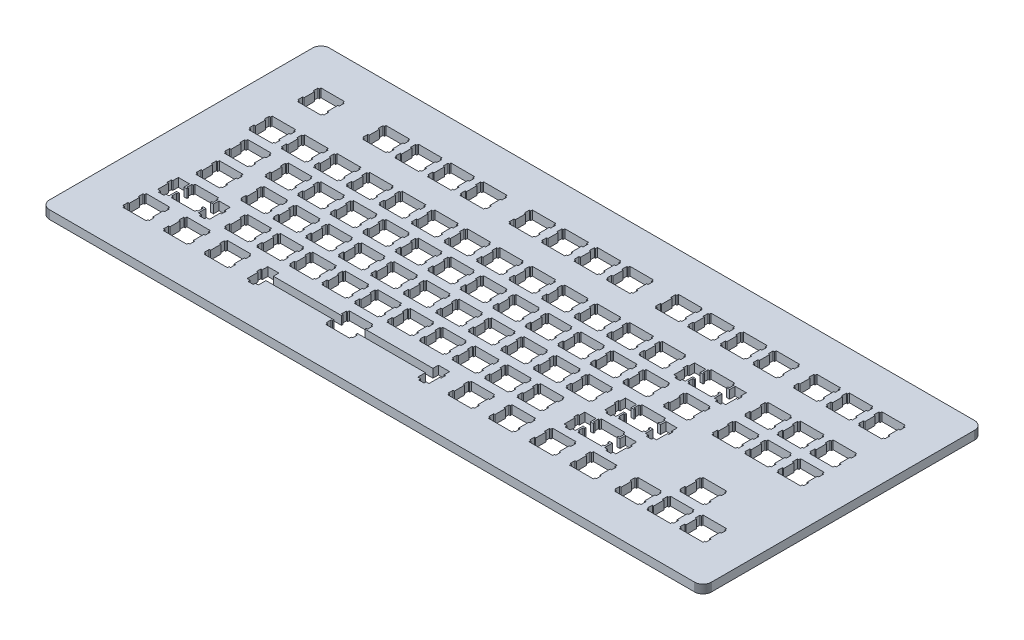
SolidWorks part; units mm, degrees
ref_plane "Front Plane" through (0, 0, 0) normal (0, 0, 1) x (1, 0, 0)
ref_plane "Top Plane" through (0, 0, 0) normal (0, 1, 0) x (1, 0, 0)
ref_plane "Right Plane" through (0, 0, 0) normal (1, 0, 0) x (0, 0, -1)
sketch "Sketch1" plane through (0, 0, 0) normal (0, 1, 0) x (1, 0, 0)
  line L0 (382.958, 164.299) -> (383.35, 164.284)
  line L1 (383.35, 164.284) -> (383.741, 164.237)
  line L2 (383.741, 164.237) -> (384.126, 164.162)
  line L3 (384.126, 164.162) -> (384.503, 164.055)
  line L4 (384.503, 164.055) -> (384.87, 163.919)
  line L5 (384.87, 163.919) -> (385.226, 163.755)
  line L6 (385.226, 163.755) -> (385.572, 163.564)
  line L7 (385.572, 163.564) -> (385.897, 163.344)
  line L8 (385.897, 163.344) -> (386.203, 163.102)
  line L9 (386.203, 163.102) -> (386.493, 162.834)
  line L10 (386.493, 162.834) -> (386.761, 162.547)
  line L11 (386.761, 162.547) -> (387.004, 162.238)
  line L12 (387.004, 162.238) -> (387.223, 161.913)
  line L13 (387.223, 161.913) -> (387.414, 161.569)
  line L14 (387.414, 161.569) -> (387.576, 161.212)
  line L15 (387.576, 161.212) -> (387.713, 160.845)
  line L16 (387.713, 160.845) -> (387.819, 160.467)
  line L17 (387.819, 160.467) -> (387.897, 160.082)
  line L18 (387.897, 160.082) -> (387.943, 159.693)
  line L19 (387.943, 159.693) -> (387.96, 159.299)
  line L20 (387.96, 159.299) -> (387.96, 5.2724)
  line L21 (387.96, 5.2724) -> (387.943, 4.881)
  line L22 (387.943, 4.881) -> (387.897, 4.491)
  line L23 (387.897, 4.491) -> (387.819, 4.1066)
  line L24 (387.819, 4.1066) -> (387.713, 3.7276)
  line L25 (387.713, 3.7276) -> (387.576, 3.3597)
  line L26 (387.576, 3.3597) -> (387.414, 3.0041)
  line L27 (387.414, 3.0041) -> (387.223, 2.661)
  line L28 (387.223, 2.661) -> (387.004, 2.3344)
  line L29 (387.004, 2.3344) -> (386.761, 2.0257)
  line L30 (386.761, 2.0257) -> (386.493, 1.7377)
  line L31 (386.493, 1.7377) -> (386.203, 1.4704)
  line L32 (386.203, 1.4704) -> (385.897, 1.2278)
  line L33 (385.897, 1.2278) -> (385.572, 1.0101)
  line L34 (385.572, 1.0101) -> (385.226, 0.8186)
  line L35 (385.226, 0.8186) -> (384.87, 0.6546)
  line L36 (384.87, 0.6546) -> (384.503, 0.5181)
  line L37 (384.503, 0.5181) -> (384.126, 0.412)
  line L38 (384.126, 0.412) -> (383.741, 0.3349)
  line L39 (383.741, 0.3349) -> (383.35, 0.2894)
  line L40 (383.35, 0.2894) -> (382.958, 0.2729)
  line L41 (382.958, 0.2729) -> (5.096, 0.2729)
  line L42 (5.096, 0.2729) -> (4.7019, 0.2894)
  line L43 (4.7019, 0.2894) -> (4.3119, 0.3349)
  line L44 (4.3119, 0.3349) -> (3.9274, 0.412)
  line L45 (3.9274, 0.412) -> (3.5498, 0.5181)
  line L46 (3.5498, 0.5181) -> (3.1819, 0.6546)
  line L47 (3.1819, 0.6546) -> (2.825, 0.8186)
  line L48 (2.825, 0.8186) -> (2.4819, 1.0101)
  line L49 (2.4819, 1.0101) -> (2.1566, 1.2278)
  line L50 (2.1566, 1.2278) -> (1.848, 1.4704)
  line L51 (1.848, 1.4704) -> (1.5599, 1.7377)
  line L52 (1.5599, 1.7377) -> (1.2926, 2.0257)
  line L53 (1.2926, 2.0257) -> (1.0501, 2.3344)
  line L54 (1.0501, 2.3344) -> (0.831, 2.661)
  line L55 (0.831, 2.661) -> (0.6394, 3.0041)
  line L56 (0.6394, 3.0041) -> (0.4754, 3.3597)
  line L57 (0.4754, 3.3597) -> (0.339, 3.7276)
  line L58 (0.339, 3.7276) -> (0.2329, 4.1066)
  line L59 (0.2329, 4.1066) -> (0.1571, 4.491)
  line L60 (0.1571, 4.491) -> (0.1102, 4.881)
  line L61 (0.1102, 4.881) -> (0.0951, 5.2737)
  line L62 (0.0951, 5.2737) -> (0.0951, 159.299)
  line L63 (0.0951, 159.299) -> (0.1102, 159.693)
  line L64 (0.1102, 159.693) -> (0.1571, 160.082)
  line L65 (0.1571, 160.082) -> (0.2329, 160.467)
  line L66 (0.2329, 160.467) -> (0.339, 160.845)
  line L67 (0.339, 160.845) -> (0.4754, 161.212)
  line L68 (0.4754, 161.212) -> (0.6394, 161.569)
  line L69 (0.6394, 161.569) -> (0.831, 161.913)
  line L70 (0.831, 161.913) -> (1.0501, 162.238)
  line L71 (1.0501, 162.238) -> (1.2926, 162.547)
  line L72 (1.2926, 162.547) -> (1.5599, 162.834)
  line L73 (1.5599, 162.834) -> (1.848, 163.102)
  line L74 (1.848, 163.102) -> (2.1566, 163.344)
  line L75 (2.1566, 163.344) -> (2.4819, 163.564)
  line L76 (2.4819, 163.564) -> (2.825, 163.755)
  line L77 (2.825, 163.755) -> (3.1819, 163.919)
  line L78 (3.1819, 163.919) -> (3.5498, 164.055)
  line L79 (3.5498, 164.055) -> (3.9274, 164.162)
  line L80 (3.9274, 164.162) -> (4.3119, 164.237)
  line L81 (4.3119, 164.237) -> (4.7019, 164.284)
  line L82 (4.7019, 164.284) -> (5.096, 164.299)
  line L83 (5.096, 164.299) -> (382.958, 164.299)
  line L84 (144.264, 36.7993) -> (144.264, 35.7988)
  line L85 (144.264, 35.7988) -> (143.463, 35.7988)
  line L86 (143.463, 35.7988) -> (143.463, 32.8993)
  line L87 (143.463, 32.8993) -> (144.264, 32.8993)
  line L88 (144.264, 32.8993) -> (144.264, 32.0986)
  line L89 (144.264, 32.0986) -> (104.439, 32.0986)
  line L90 (104.439, 32.0986) -> (104.439, 35.3289)
  line L91 (104.439, 35.3289) -> (97.8888, 35.3289)
  line L92 (97.8888, 35.3289) -> (97.8888, 32.0986)
  line L93 (97.8888, 32.0986) -> (97.0636, 32.0986)
  line L94 (97.0636, 32.0986) -> (97.0636, 29.4983)
  line L95 (97.0636, 29.4983) -> (97.8888, 29.4983)
  line L96 (97.8888, 29.4983) -> (97.8888, 23.2296)
  line L97 (97.8888, 23.2296) -> (99.6128, 23.2296)
  line L98 (99.6128, 23.2296) -> (99.6128, 22.0293)
  line L99 (99.6128, 22.0293) -> (102.713, 22.0293)
  line L100 (102.713, 22.0293) -> (102.713, 23.2296)
  line L101 (102.713, 23.2296) -> (104.439, 23.2296)
  line L102 (104.439, 23.2296) -> (104.439, 27.6986)
  line L103 (104.439, 27.6986) -> (144.264, 27.6986)
  line L104 (144.264, 27.6986) -> (144.264, 26.8993)
  line L105 (144.264, 26.8993) -> (143.463, 26.8993)
  line L106 (143.463, 26.8993) -> (143.463, 23.9985)
  line L107 (143.463, 23.9985) -> (144.264, 23.9985)
  line L108 (144.264, 23.9985) -> (144.264, 22.9995)
  line L109 (144.264, 22.9995) -> (158.064, 22.9995)
  line L110 (158.064, 22.9995) -> (158.064, 23.9985)
  line L111 (158.064, 23.9985) -> (158.863, 23.9985)
  line L112 (158.863, 23.9985) -> (158.863, 26.8993)
  line L113 (158.863, 26.8993) -> (158.064, 26.8993)
  line L114 (158.064, 26.8993) -> (158.064, 27.6986)
  line L115 (158.064, 27.6986) -> (197.889, 27.6986)
  line L116 (197.889, 27.6986) -> (197.889, 23.2296)
  line L117 (197.889, 23.2296) -> (199.613, 23.2296)
  line L118 (199.613, 23.2296) -> (199.613, 22.0293)
  line L119 (199.613, 22.0293) -> (202.714, 22.0293)
  line L120 (202.714, 22.0293) -> (202.714, 23.2296)
  line L121 (202.714, 23.2296) -> (204.439, 23.2296)
  line L122 (204.439, 23.2296) -> (204.439, 29.4983)
  line L123 (204.439, 29.4983) -> (205.263, 29.4983)
  line L124 (205.263, 29.4983) -> (205.263, 32.0986)
  line L125 (205.263, 32.0986) -> (204.439, 32.0986)
  line L126 (204.439, 32.0986) -> (204.439, 35.3289)
  line L127 (204.439, 35.3289) -> (197.889, 35.3289)
  line L128 (197.889, 35.3289) -> (197.889, 32.0986)
  line L129 (197.889, 32.0986) -> (158.064, 32.0986)
  line L130 (158.064, 32.0986) -> (158.064, 32.8993)
  line L131 (158.064, 32.8993) -> (158.863, 32.8993)
  line L132 (158.863, 32.8993) -> (158.863, 35.7988)
  line L133 (158.863, 35.7988) -> (158.064, 35.7988)
  line L134 (158.064, 35.7988) -> (158.064, 36.7993)
  line L135 (158.064, 36.7993) -> (144.264, 36.7993)
  line L136 (351.433, 36.7993) -> (351.433, 35.7988)
  line L137 (351.433, 35.7988) -> (350.632, 35.7988)
  line L138 (350.632, 35.7988) -> (350.632, 32.8993)
  line L139 (350.632, 32.8993) -> (351.433, 32.8993)
  line L140 (351.433, 32.8993) -> (351.433, 26.8993)
  line L141 (351.433, 26.8993) -> (350.632, 26.8993)
  line L142 (350.632, 26.8993) -> (350.632, 23.9985)
  line L143 (350.632, 23.9985) -> (351.433, 23.9985)
  line L144 (351.433, 23.9985) -> (351.433, 22.9995)
  line L145 (351.433, 22.9995) -> (365.231, 22.9995)
  line L146 (365.231, 22.9995) -> (365.231, 23.9985)
  line L147 (365.231, 23.9985) -> (366.032, 23.9985)
  line L148 (366.032, 23.9985) -> (366.032, 26.8993)
  line L149 (366.032, 26.8993) -> (365.231, 26.8993)
  line L150 (365.231, 26.8993) -> (365.231, 32.8993)
  line L151 (365.231, 32.8993) -> (366.032, 32.8993)
  line L152 (366.032, 32.8993) -> (366.032, 35.7988)
  line L153 (366.032, 35.7988) -> (365.231, 35.7988)
  line L154 (365.231, 35.7988) -> (365.231, 36.7993)
  line L155 (365.231, 36.7993) -> (351.433, 36.7993)
  line L156 (332.383, 36.7993) -> (332.383, 35.7988)
  line L157 (332.383, 35.7988) -> (331.582, 35.7988)
  line L158 (331.582, 35.7988) -> (331.582, 32.8993)
  line L159 (331.582, 32.8993) -> (332.383, 32.8993)
  line L160 (332.383, 32.8993) -> (332.383, 26.8993)
  line L161 (332.383, 26.8993) -> (331.582, 26.8993)
  line L162 (331.582, 26.8993) -> (331.582, 23.9985)
  line L163 (331.582, 23.9985) -> (332.383, 23.9985)
  line L164 (332.383, 23.9985) -> (332.383, 22.9995)
  line L165 (332.383, 22.9995) -> (346.183, 22.9995)
  line L166 (346.183, 22.9995) -> (346.183, 23.9985)
  line L167 (346.183, 23.9985) -> (346.983, 23.9985)
  line L168 (346.983, 23.9985) -> (346.983, 26.8993)
  line L169 (346.983, 26.8993) -> (346.183, 26.8993)
  line L170 (346.183, 26.8993) -> (346.183, 32.8993)
  line L171 (346.183, 32.8993) -> (346.983, 32.8993)
  line L172 (346.983, 32.8993) -> (346.983, 35.7988)
  line L173 (346.983, 35.7988) -> (346.183, 35.7988)
  line L174 (346.183, 35.7988) -> (346.183, 36.7993)
  line L175 (346.183, 36.7993) -> (332.383, 36.7993)
  line L176 (313.333, 36.7993) -> (313.333, 35.7988)
  line L177 (313.333, 35.7988) -> (312.532, 35.7988)
  line L178 (312.532, 35.7988) -> (312.532, 32.8993)
  line L179 (312.532, 32.8993) -> (313.333, 32.8993)
  line L180 (313.333, 32.8993) -> (313.333, 26.8993)
  line L181 (313.333, 26.8993) -> (312.532, 26.8993)
  line L182 (312.532, 26.8993) -> (312.532, 23.9985)
  line L183 (312.532, 23.9985) -> (313.333, 23.9985)
  line L184 (313.333, 23.9985) -> (313.333, 22.9995)
  line L185 (313.333, 22.9995) -> (327.133, 22.9995)
  line L186 (327.133, 22.9995) -> (327.133, 23.9985)
  line L187 (327.133, 23.9985) -> (327.933, 23.9985)
  line L188 (327.933, 23.9985) -> (327.933, 26.8993)
  line L189 (327.933, 26.8993) -> (327.133, 26.8993)
  line L190 (327.133, 26.8993) -> (327.133, 32.8993)
  line L191 (327.133, 32.8993) -> (327.933, 32.8993)
  line L192 (327.933, 32.8993) -> (327.933, 35.7988)
  line L193 (327.933, 35.7988) -> (327.133, 35.7988)
  line L194 (327.133, 35.7988) -> (327.133, 36.7993)
  line L195 (327.133, 36.7993) -> (313.333, 36.7993)
  line L196 (287.139, 36.7993) -> (287.139, 35.7988)
  line L197 (287.139, 35.7988) -> (286.338, 35.7988)
  line L198 (286.338, 35.7988) -> (286.338, 32.8993)
  line L199 (286.338, 32.8993) -> (287.139, 32.8993)
  line L200 (287.139, 32.8993) -> (287.139, 26.8993)
  line L201 (287.139, 26.8993) -> (286.338, 26.8993)
  line L202 (286.338, 26.8993) -> (286.338, 23.9985)
  line L203 (286.338, 23.9985) -> (287.139, 23.9985)
  line L204 (287.139, 23.9985) -> (287.139, 22.9995)
  line L205 (287.139, 22.9995) -> (300.939, 22.9995)
  line L206 (300.939, 22.9995) -> (300.939, 23.9985)
  line L207 (300.939, 23.9985) -> (301.738, 23.9985)
  line L208 (301.738, 23.9985) -> (301.738, 26.8993)
  line L209 (301.738, 26.8993) -> (300.939, 26.8993)
  line L210 (300.939, 26.8993) -> (300.939, 32.8993)
  line L211 (300.939, 32.8993) -> (301.738, 32.8993)
  line L212 (301.738, 32.8993) -> (301.738, 35.7988)
  line L213 (301.738, 35.7988) -> (300.939, 35.7988)
  line L214 (300.939, 35.7988) -> (300.939, 36.7993)
  line L215 (300.939, 36.7993) -> (287.139, 36.7993)
  line L216 (263.327, 36.7993) -> (263.327, 35.7988)
  line L217 (263.327, 35.7988) -> (262.526, 35.7988)
  line L218 (262.526, 35.7988) -> (262.526, 32.8993)
  line L219 (262.526, 32.8993) -> (263.327, 32.8993)
  line L220 (263.327, 32.8993) -> (263.327, 26.8993)
  line L221 (263.327, 26.8993) -> (262.526, 26.8993)
  line L222 (262.526, 26.8993) -> (262.526, 23.9985)
  line L223 (262.526, 23.9985) -> (263.327, 23.9985)
  line L224 (263.327, 23.9985) -> (263.327, 22.9995)
  line L225 (263.327, 22.9995) -> (277.126, 22.9995)
  line L226 (277.126, 22.9995) -> (277.126, 23.9985)
  line L227 (277.126, 23.9985) -> (277.927, 23.9985)
  line L228 (277.927, 23.9985) -> (277.927, 26.8993)
  line L229 (277.927, 26.8993) -> (277.126, 26.8993)
  line L230 (277.126, 26.8993) -> (277.126, 32.8993)
  line L231 (277.126, 32.8993) -> (277.927, 32.8993)
  line L232 (277.927, 32.8993) -> (277.927, 35.7988)
  line L233 (277.927, 35.7988) -> (277.126, 35.7988)
  line L234 (277.126, 35.7988) -> (277.126, 36.7993)
  line L235 (277.126, 36.7993) -> (263.327, 36.7993)
  line L236 (239.514, 36.7993) -> (239.514, 35.7988)
  line L237 (239.514, 35.7988) -> (238.713, 35.7988)
  line L238 (238.713, 35.7988) -> (238.713, 32.8993)
  line L239 (238.713, 32.8993) -> (239.514, 32.8993)
  line L240 (239.514, 32.8993) -> (239.514, 26.8993)
  line L241 (239.514, 26.8993) -> (238.713, 26.8993)
  line L242 (238.713, 26.8993) -> (238.713, 23.9985)
  line L243 (238.713, 23.9985) -> (239.514, 23.9985)
  line L244 (239.514, 23.9985) -> (239.514, 22.9995)
  line L245 (239.514, 22.9995) -> (253.314, 22.9995)
  line L246 (253.314, 22.9995) -> (253.314, 23.9985)
  line L247 (253.314, 23.9985) -> (254.113, 23.9985)
  line L248 (254.113, 23.9985) -> (254.113, 26.8993)
  line L249 (254.113, 26.8993) -> (253.314, 26.8993)
  line L250 (253.314, 26.8993) -> (253.314, 32.8993)
  line L251 (253.314, 32.8993) -> (254.113, 32.8993)
  line L252 (254.113, 32.8993) -> (254.113, 35.7988)
  line L253 (254.113, 35.7988) -> (253.314, 35.7988)
  line L254 (253.314, 35.7988) -> (253.314, 36.7993)
  line L255 (253.314, 36.7993) -> (239.514, 36.7993)
  line L256 (215.702, 36.7993) -> (215.702, 35.7988)
  line L257 (215.702, 35.7988) -> (214.901, 35.7988)
  line L258 (214.901, 35.7988) -> (214.901, 32.8993)
  line L259 (214.901, 32.8993) -> (215.702, 32.8993)
  line L260 (215.702, 32.8993) -> (215.702, 26.8993)
  line L261 (215.702, 26.8993) -> (214.901, 26.8993)
  line L262 (214.901, 26.8993) -> (214.901, 23.9985)
  line L263 (214.901, 23.9985) -> (215.702, 23.9985)
  line L264 (215.702, 23.9985) -> (215.702, 22.9995)
  line L265 (215.702, 22.9995) -> (229.501, 22.9995)
  line L266 (229.501, 22.9995) -> (229.501, 23.9985)
  line L267 (229.501, 23.9985) -> (230.302, 23.9985)
  line L268 (230.302, 23.9985) -> (230.302, 26.8993)
  line L269 (230.302, 26.8993) -> (229.501, 26.8993)
  line L270 (229.501, 26.8993) -> (229.501, 32.8993)
  line L271 (229.501, 32.8993) -> (230.302, 32.8993)
  line L272 (230.302, 32.8993) -> (230.302, 35.7988)
  line L273 (230.302, 35.7988) -> (229.501, 35.7988)
  line L274 (229.501, 35.7988) -> (229.501, 36.7993)
  line L275 (229.501, 36.7993) -> (215.702, 36.7993)
  line L276 (72.8267, 36.7993) -> (72.8267, 35.7988)
  line L277 (72.8267, 35.7988) -> (72.0259, 35.7988)
  line L278 (72.0259, 35.7988) -> (72.0259, 32.8993)
  line L279 (72.0259, 32.8993) -> (72.8267, 32.8993)
  line L280 (72.8267, 32.8993) -> (72.8267, 26.8993)
  line L281 (72.8267, 26.8993) -> (72.0259, 26.8993)
  line L282 (72.0259, 26.8993) -> (72.0259, 23.9985)
  line L283 (72.0259, 23.9985) -> (72.8267, 23.9985)
  line L284 (72.8267, 23.9985) -> (72.8267, 22.9995)
  line L285 (72.8267, 22.9995) -> (86.6263, 22.9995)
  line L286 (86.6263, 22.9995) -> (86.6263, 23.9985)
  line L287 (86.6263, 23.9985) -> (87.4268, 23.9985)
  line L288 (87.4268, 23.9985) -> (87.4268, 26.8993)
  line L289 (87.4268, 26.8993) -> (86.6263, 26.8993)
  line L290 (86.6263, 26.8993) -> (86.6263, 32.8993)
  line L291 (86.6263, 32.8993) -> (87.4268, 32.8993)
  line L292 (87.4268, 32.8993) -> (87.4268, 35.7988)
  line L293 (87.4268, 35.7988) -> (86.6263, 35.7988)
  line L294 (86.6263, 35.7988) -> (86.6263, 36.7993)
  line L295 (86.6263, 36.7993) -> (72.8267, 36.7993)
  line L296 (49.0142, 36.7993) -> (49.0142, 35.7988)
  line L297 (49.0142, 35.7988) -> (48.2134, 35.7988)
  line L298 (48.2134, 35.7988) -> (48.2134, 32.8993)
  line L299 (48.2134, 32.8993) -> (49.0142, 32.8993)
  line L300 (49.0142, 32.8993) -> (49.0142, 26.8993)
  line L301 (49.0142, 26.8993) -> (48.2134, 26.8993)
  line L302 (48.2134, 26.8993) -> (48.2134, 23.9985)
  line L303 (48.2134, 23.9985) -> (49.0142, 23.9985)
  line L304 (49.0142, 23.9985) -> (49.0142, 22.9995)
  line L305 (49.0142, 22.9995) -> (62.8138, 22.9995)
  line L306 (62.8138, 22.9995) -> (62.8138, 23.9985)
  line L307 (62.8138, 23.9985) -> (63.6129, 23.9985)
  line L308 (63.6129, 23.9985) -> (63.6129, 26.8993)
  line L309 (63.6129, 26.8993) -> (62.8138, 26.8993)
  line L310 (62.8138, 26.8993) -> (62.8138, 32.8993)
  line L311 (62.8138, 32.8993) -> (63.6129, 32.8993)
  line L312 (63.6129, 32.8993) -> (63.6129, 35.7988)
  line L313 (63.6129, 35.7988) -> (62.8138, 35.7988)
  line L314 (62.8138, 35.7988) -> (62.8138, 36.7993)
  line L315 (62.8138, 36.7993) -> (49.0142, 36.7993)
  line L316 (25.2016, 36.7993) -> (25.2016, 35.7988)
  line L317 (25.2016, 35.7988) -> (24.4009, 35.7988)
  line L318 (24.4009, 35.7988) -> (24.4009, 32.8993)
  line L319 (24.4009, 32.8993) -> (25.2016, 32.8993)
  line L320 (25.2016, 32.8993) -> (25.2016, 26.8993)
  line L321 (25.2016, 26.8993) -> (24.4009, 26.8993)
  line L322 (24.4009, 26.8993) -> (24.4009, 23.9985)
  line L323 (24.4009, 23.9985) -> (25.2016, 23.9985)
  line L324 (25.2016, 23.9985) -> (25.2016, 22.9995)
  line L325 (25.2016, 22.9995) -> (39.0013, 22.9995)
  line L326 (39.0013, 22.9995) -> (39.0013, 23.9985)
  line L327 (39.0013, 23.9985) -> (39.8018, 23.9985)
  line L328 (39.8018, 23.9985) -> (39.8018, 26.8993)
  line L329 (39.8018, 26.8993) -> (39.0013, 26.8993)
  line L330 (39.0013, 26.8993) -> (39.0013, 32.8993)
  line L331 (39.0013, 32.8993) -> (39.8018, 32.8993)
  line L332 (39.8018, 32.8993) -> (39.8018, 35.7988)
  line L333 (39.8018, 35.7988) -> (39.0013, 35.7988)
  line L334 (39.0013, 35.7988) -> (39.0013, 36.7993)
  line L335 (39.0013, 36.7993) -> (25.2016, 36.7993)
  line L336 (272.852, 55.8504) -> (272.852, 54.8499)
  line L337 (272.852, 54.8499) -> (272.051, 54.8499)
  line L338 (272.051, 54.8499) -> (272.051, 51.9493)
  line L339 (272.051, 51.9493) -> (272.852, 51.9493)
  line L340 (272.852, 51.9493) -> (272.852, 51.15)
  line L341 (272.852, 51.15) -> (271.126, 51.15)
  line L342 (271.126, 51.15) -> (271.126, 54.38)
  line L343 (271.126, 54.38) -> (264.576, 54.38)
  line L344 (264.576, 54.38) -> (264.576, 51.15)
  line L345 (264.576, 51.15) -> (263.751, 51.15)
  line L346 (263.751, 51.15) -> (263.751, 48.5482)
  line L347 (263.751, 48.5482) -> (264.576, 48.5482)
  line L348 (264.576, 48.5482) -> (264.576, 42.2797)
  line L349 (264.576, 42.2797) -> (266.302, 42.2797)
  line L350 (266.302, 42.2797) -> (266.302, 41.0792)
  line L351 (266.302, 41.0792) -> (269.401, 41.0792)
  line L352 (269.401, 41.0792) -> (269.401, 42.2797)
  line L353 (269.401, 42.2797) -> (271.126, 42.2797)
  line L354 (271.126, 42.2797) -> (271.126, 46.7487)
  line L355 (271.126, 46.7487) -> (272.852, 46.7487)
  line L356 (272.852, 46.7487) -> (272.852, 45.9493)
  line L357 (272.852, 45.9493) -> (272.051, 45.9493)
  line L358 (272.051, 45.9493) -> (272.051, 43.0484)
  line L359 (272.051, 43.0484) -> (272.852, 43.0484)
  line L360 (272.852, 43.0484) -> (272.852, 42.0493)
  line L361 (272.852, 42.0493) -> (286.651, 42.0493)
  line L362 (286.651, 42.0493) -> (286.651, 43.0484)
  line L363 (286.651, 43.0484) -> (287.452, 43.0484)
  line L364 (287.452, 43.0484) -> (287.452, 45.9493)
  line L365 (287.452, 45.9493) -> (286.651, 45.9493)
  line L366 (286.651, 45.9493) -> (286.651, 46.7487)
  line L367 (286.651, 46.7487) -> (288.376, 46.7487)
  line L368 (288.376, 46.7487) -> (288.376, 42.2797)
  line L369 (288.376, 42.2797) -> (290.102, 42.2797)
  line L370 (290.102, 42.2797) -> (290.102, 41.0792)
  line L371 (290.102, 41.0792) -> (293.201, 41.0792)
  line L372 (293.201, 41.0792) -> (293.201, 42.2797)
  line L373 (293.201, 42.2797) -> (294.926, 42.2797)
  line L374 (294.926, 42.2797) -> (294.926, 48.5482)
  line L375 (294.926, 48.5482) -> (295.752, 48.5482)
  line L376 (295.752, 48.5482) -> (295.752, 51.15)
  line L377 (295.752, 51.15) -> (294.926, 51.15)
  line L378 (294.926, 51.15) -> (294.926, 54.38)
  line L379 (294.926, 54.38) -> (288.376, 54.38)
  line L380 (288.376, 54.38) -> (288.376, 51.15)
  line L381 (288.376, 51.15) -> (286.651, 51.15)
  line L382 (286.651, 51.15) -> (286.651, 51.9493)
  line L383 (286.651, 51.9493) -> (287.452, 51.9493)
  line L384 (287.452, 51.9493) -> (287.452, 54.8499)
  line L385 (287.452, 54.8499) -> (286.651, 54.8499)
  line L386 (286.651, 54.8499) -> (286.651, 55.8504)
  line L387 (286.651, 55.8504) -> (272.852, 55.8504)
  line L388 (34.7266, 55.8504) -> (34.7266, 54.8499)
  line L389 (34.7266, 54.8499) -> (33.9259, 54.8499)
  line L390 (33.9259, 54.8499) -> (33.9259, 51.9493)
  line L391 (33.9259, 51.9493) -> (34.7266, 51.9493)
  line L392 (34.7266, 51.9493) -> (34.7266, 51.15)
  line L393 (34.7266, 51.15) -> (33.0013, 51.15)
  line L394 (33.0013, 51.15) -> (33.0013, 54.38)
  line L395 (33.0013, 54.38) -> (26.4515, 54.38)
  line L396 (26.4515, 54.38) -> (26.4515, 51.15)
  line L397 (26.4515, 51.15) -> (25.626, 51.15)
  line L398 (25.626, 51.15) -> (25.626, 48.5482)
  line L399 (25.626, 48.5482) -> (26.4515, 48.5482)
  line L400 (26.4515, 48.5482) -> (26.4515, 42.2797)
  line L401 (26.4515, 42.2797) -> (28.1767, 42.2797)
  line L402 (28.1767, 42.2797) -> (28.1767, 41.0792)
  line L403 (28.1767, 41.0792) -> (31.276, 41.0792)
  line L404 (31.276, 41.0792) -> (31.276, 42.2797)
  line L405 (31.276, 42.2797) -> (33.0013, 42.2797)
  line L406 (33.0013, 42.2797) -> (33.0013, 46.7487)
  line L407 (33.0013, 46.7487) -> (34.7266, 46.7487)
  line L408 (34.7266, 46.7487) -> (34.7266, 45.9493)
  line L409 (34.7266, 45.9493) -> (33.9259, 45.9493)
  line L410 (33.9259, 45.9493) -> (33.9259, 43.0484)
  line L411 (33.9259, 43.0484) -> (34.7266, 43.0484)
  line L412 (34.7266, 43.0484) -> (34.7266, 42.0493)
  line L413 (34.7266, 42.0493) -> (48.5263, 42.0493)
  line L414 (48.5263, 42.0493) -> (48.5263, 43.0484)
  line L415 (48.5263, 43.0484) -> (49.3268, 43.0484)
  line L416 (49.3268, 43.0484) -> (49.3268, 45.9493)
  line L417 (49.3268, 45.9493) -> (48.5263, 45.9493)
  line L418 (48.5263, 45.9493) -> (48.5263, 46.7487)
  line L419 (48.5263, 46.7487) -> (50.2514, 46.7487)
  line L420 (50.2514, 46.7487) -> (50.2514, 42.2797)
  line L421 (50.2514, 42.2797) -> (51.9769, 42.2797)
  line L422 (51.9769, 42.2797) -> (51.9769, 41.0792)
  line L423 (51.9769, 41.0792) -> (55.076, 41.0792)
  line L424 (55.076, 41.0792) -> (55.076, 42.2797)
  line L425 (55.076, 42.2797) -> (56.8015, 42.2797)
  line L426 (56.8015, 42.2797) -> (56.8015, 48.5482)
  line L427 (56.8015, 48.5482) -> (57.627, 48.5482)
  line L428 (57.627, 48.5482) -> (57.627, 51.15)
  line L429 (57.627, 51.15) -> (56.8015, 51.15)
  line L430 (56.8015, 51.15) -> (56.8015, 54.38)
  line L431 (56.8015, 54.38) -> (50.2514, 54.38)
  line L432 (50.2514, 54.38) -> (50.2514, 51.15)
  line L433 (50.2514, 51.15) -> (48.5263, 51.15)
  line L434 (48.5263, 51.15) -> (48.5263, 51.9493)
  line L435 (48.5263, 51.9493) -> (49.3268, 51.9493)
  line L436 (49.3268, 51.9493) -> (49.3268, 54.8499)
  line L437 (49.3268, 54.8499) -> (48.5263, 54.8499)
  line L438 (48.5263, 54.8499) -> (48.5263, 55.8504)
  line L439 (48.5263, 55.8504) -> (34.7266, 55.8504)
  line L440 (332.383, 55.8504) -> (332.383, 54.8499)
  line L441 (332.383, 54.8499) -> (331.582, 54.8499)
  line L442 (331.582, 54.8499) -> (331.582, 51.9493)
  line L443 (331.582, 51.9493) -> (332.383, 51.9493)
  line L444 (332.383, 51.9493) -> (332.383, 45.9493)
  line L445 (332.383, 45.9493) -> (331.582, 45.9493)
  line L446 (331.582, 45.9493) -> (331.582, 43.0484)
  line L447 (331.582, 43.0484) -> (332.383, 43.0484)
  line L448 (332.383, 43.0484) -> (332.383, 42.0493)
  line L449 (332.383, 42.0493) -> (346.183, 42.0493)
  line L450 (346.183, 42.0493) -> (346.183, 43.0484)
  line L451 (346.183, 43.0484) -> (346.983, 43.0484)
  line L452 (346.983, 43.0484) -> (346.983, 45.9493)
  line L453 (346.983, 45.9493) -> (346.183, 45.9493)
  line L454 (346.183, 45.9493) -> (346.183, 51.9493)
  line L455 (346.183, 51.9493) -> (346.983, 51.9493)
  line L456 (346.983, 51.9493) -> (346.983, 54.8499)
  line L457 (346.983, 54.8499) -> (346.183, 54.8499)
  line L458 (346.183, 54.8499) -> (346.183, 55.8504)
  line L459 (346.183, 55.8504) -> (332.383, 55.8504)
  line L460 (237.133, 55.8504) -> (237.133, 54.8499)
  line L461 (237.133, 54.8499) -> (236.332, 54.8499)
  line L462 (236.332, 54.8499) -> (236.332, 51.9493)
  line L463 (236.332, 51.9493) -> (237.133, 51.9493)
  line L464 (237.133, 51.9493) -> (237.133, 45.9493)
  line L465 (237.133, 45.9493) -> (236.332, 45.9493)
  line L466 (236.332, 45.9493) -> (236.332, 43.0484)
  line L467 (236.332, 43.0484) -> (237.133, 43.0484)
  line L468 (237.133, 43.0484) -> (237.133, 42.0493)
  line L469 (237.133, 42.0493) -> (250.933, 42.0493)
  line L470 (250.933, 42.0493) -> (250.933, 43.0484)
  line L471 (250.933, 43.0484) -> (251.733, 43.0484)
  line L472 (251.733, 43.0484) -> (251.733, 45.9493)
  line L473 (251.733, 45.9493) -> (250.933, 45.9493)
  line L474 (250.933, 45.9493) -> (250.933, 51.9493)
  line L475 (250.933, 51.9493) -> (251.733, 51.9493)
  line L476 (251.733, 51.9493) -> (251.733, 54.8499)
  line L477 (251.733, 54.8499) -> (250.933, 54.8499)
  line L478 (250.933, 54.8499) -> (250.933, 55.8504)
  line L479 (250.933, 55.8504) -> (237.133, 55.8504)
  line L480 (218.083, 55.8504) -> (218.083, 54.8499)
  line L481 (218.083, 54.8499) -> (217.282, 54.8499)
  line L482 (217.282, 54.8499) -> (217.282, 51.9493)
  line L483 (217.282, 51.9493) -> (218.083, 51.9493)
  line L484 (218.083, 51.9493) -> (218.083, 45.9493)
  line L485 (218.083, 45.9493) -> (217.282, 45.9493)
  line L486 (217.282, 45.9493) -> (217.282, 43.0484)
  line L487 (217.282, 43.0484) -> (218.083, 43.0484)
  line L488 (218.083, 43.0484) -> (218.083, 42.0493)
  line L489 (218.083, 42.0493) -> (231.883, 42.0493)
  line L490 (231.883, 42.0493) -> (231.883, 43.0484)
  line L491 (231.883, 43.0484) -> (232.683, 43.0484)
  line L492 (232.683, 43.0484) -> (232.683, 45.9493)
  line L493 (232.683, 45.9493) -> (231.883, 45.9493)
  line L494 (231.883, 45.9493) -> (231.883, 51.9493)
  line L495 (231.883, 51.9493) -> (232.683, 51.9493)
  line L496 (232.683, 51.9493) -> (232.683, 54.8499)
  line L497 (232.683, 54.8499) -> (231.883, 54.8499)
  line L498 (231.883, 54.8499) -> (231.883, 55.8504)
  line L499 (231.883, 55.8504) -> (218.083, 55.8504)
  line L500 (199.033, 55.8504) -> (199.033, 54.8499)
  line L501 (199.033, 54.8499) -> (198.232, 54.8499)
  line L502 (198.232, 54.8499) -> (198.232, 51.9493)
  line L503 (198.232, 51.9493) -> (199.033, 51.9493)
  line L504 (199.033, 51.9493) -> (199.033, 45.9493)
  line L505 (199.033, 45.9493) -> (198.232, 45.9493)
  line L506 (198.232, 45.9493) -> (198.232, 43.0484)
  line L507 (198.232, 43.0484) -> (199.033, 43.0484)
  line L508 (199.033, 43.0484) -> (199.033, 42.0493)
  line L509 (199.033, 42.0493) -> (212.833, 42.0493)
  line L510 (212.833, 42.0493) -> (212.833, 43.0484)
  line L511 (212.833, 43.0484) -> (213.633, 43.0484)
  line L512 (213.633, 43.0484) -> (213.633, 45.9493)
  line L513 (213.633, 45.9493) -> (212.833, 45.9493)
  line L514 (212.833, 45.9493) -> (212.833, 51.9493)
  line L515 (212.833, 51.9493) -> (213.633, 51.9493)
  line L516 (213.633, 51.9493) -> (213.633, 54.8499)
  line L517 (213.633, 54.8499) -> (212.833, 54.8499)
  line L518 (212.833, 54.8499) -> (212.833, 55.8504)
  line L519 (212.833, 55.8504) -> (199.033, 55.8504)
  line L520 (179.983, 55.8504) -> (179.983, 54.8499)
  line L521 (179.983, 54.8499) -> (179.182, 54.8499)
  line L522 (179.182, 54.8499) -> (179.182, 51.9493)
  line L523 (179.182, 51.9493) -> (179.983, 51.9493)
  line L524 (179.983, 51.9493) -> (179.983, 45.9493)
  line L525 (179.983, 45.9493) -> (179.182, 45.9493)
  line L526 (179.182, 45.9493) -> (179.182, 43.0484)
  line L527 (179.182, 43.0484) -> (179.983, 43.0484)
  line L528 (179.983, 43.0484) -> (179.983, 42.0493)
  line L529 (179.983, 42.0493) -> (193.783, 42.0493)
  line L530 (193.783, 42.0493) -> (193.783, 43.0484)
  line L531 (193.783, 43.0484) -> (194.583, 43.0484)
  line L532 (194.583, 43.0484) -> (194.583, 45.9493)
  line L533 (194.583, 45.9493) -> (193.783, 45.9493)
  line L534 (193.783, 45.9493) -> (193.783, 51.9493)
  line L535 (193.783, 51.9493) -> (194.583, 51.9493)
  line L536 (194.583, 51.9493) -> (194.583, 54.8499)
  line L537 (194.583, 54.8499) -> (193.783, 54.8499)
  line L538 (193.783, 54.8499) -> (193.783, 55.8504)
  line L539 (193.783, 55.8504) -> (179.983, 55.8504)
  line L540 (160.933, 55.8504) -> (160.933, 54.8499)
  line L541 (160.933, 54.8499) -> (160.132, 54.8499)
  line L542 (160.132, 54.8499) -> (160.132, 51.9493)
  line L543 (160.132, 51.9493) -> (160.933, 51.9493)
  line L544 (160.933, 51.9493) -> (160.933, 45.9493)
  line L545 (160.933, 45.9493) -> (160.132, 45.9493)
  line L546 (160.132, 45.9493) -> (160.132, 43.0484)
  line L547 (160.132, 43.0484) -> (160.933, 43.0484)
  line L548 (160.933, 43.0484) -> (160.933, 42.0493)
  line L549 (160.933, 42.0493) -> (174.733, 42.0493)
  line L550 (174.733, 42.0493) -> (174.733, 43.0484)
  line L551 (174.733, 43.0484) -> (175.533, 43.0484)
  line L552 (175.533, 43.0484) -> (175.533, 45.9493)
  line L553 (175.533, 45.9493) -> (174.733, 45.9493)
  line L554 (174.733, 45.9493) -> (174.733, 51.9493)
  line L555 (174.733, 51.9493) -> (175.533, 51.9493)
  line L556 (175.533, 51.9493) -> (175.533, 54.8499)
  line L557 (175.533, 54.8499) -> (174.733, 54.8499)
  line L558 (174.733, 54.8499) -> (174.733, 55.8504)
  line L559 (174.733, 55.8504) -> (160.933, 55.8504)
  line L560 (141.883, 55.8504) -> (141.883, 54.8499)
  line L561 (141.883, 54.8499) -> (141.082, 54.8499)
  line L562 (141.082, 54.8499) -> (141.082, 51.9493)
  line L563 (141.082, 51.9493) -> (141.883, 51.9493)
  line L564 (141.883, 51.9493) -> (141.883, 45.9493)
  line L565 (141.883, 45.9493) -> (141.082, 45.9493)
  line L566 (141.082, 45.9493) -> (141.082, 43.0484)
  line L567 (141.082, 43.0484) -> (141.883, 43.0484)
  line L568 (141.883, 43.0484) -> (141.883, 42.0493)
  line L569 (141.883, 42.0493) -> (155.683, 42.0493)
  line L570 (155.683, 42.0493) -> (155.683, 43.0484)
  line L571 (155.683, 43.0484) -> (156.483, 43.0484)
  line L572 (156.483, 43.0484) -> (156.483, 45.9493)
  line L573 (156.483, 45.9493) -> (155.683, 45.9493)
  line L574 (155.683, 45.9493) -> (155.683, 51.9493)
  line L575 (155.683, 51.9493) -> (156.483, 51.9493)
  line L576 (156.483, 51.9493) -> (156.483, 54.8499)
  line L577 (156.483, 54.8499) -> (155.683, 54.8499)
  line L578 (155.683, 54.8499) -> (155.683, 55.8504)
  line L579 (155.683, 55.8504) -> (141.883, 55.8504)
  line L580 (122.833, 55.8504) -> (122.833, 54.8499)
  line L581 (122.833, 54.8499) -> (122.032, 54.8499)
  line L582 (122.032, 54.8499) -> (122.032, 51.9493)
  line L583 (122.032, 51.9493) -> (122.833, 51.9493)
  line L584 (122.833, 51.9493) -> (122.833, 45.9493)
  line L585 (122.833, 45.9493) -> (122.032, 45.9493)
  line L586 (122.032, 45.9493) -> (122.032, 43.0484)
  line L587 (122.032, 43.0484) -> (122.833, 43.0484)
  line L588 (122.833, 43.0484) -> (122.833, 42.0493)
  line L589 (122.833, 42.0493) -> (136.633, 42.0493)
  line L590 (136.633, 42.0493) -> (136.633, 43.0484)
  line L591 (136.633, 43.0484) -> (137.433, 43.0484)
  line L592 (137.433, 43.0484) -> (137.433, 45.9493)
  line L593 (137.433, 45.9493) -> (136.633, 45.9493)
  line L594 (136.633, 45.9493) -> (136.633, 51.9493)
  line L595 (136.633, 51.9493) -> (137.433, 51.9493)
  line L596 (137.433, 51.9493) -> (137.433, 54.8499)
  line L597 (137.433, 54.8499) -> (136.633, 54.8499)
  line L598 (136.633, 54.8499) -> (136.633, 55.8504)
  line L599 (136.633, 55.8504) -> (122.833, 55.8504)
  line L600 (103.783, 55.8504) -> (103.783, 54.8499)
  line L601 (103.783, 54.8499) -> (102.982, 54.8499)
  line L602 (102.982, 54.8499) -> (102.982, 51.9493)
  line L603 (102.982, 51.9493) -> (103.783, 51.9493)
  line L604 (103.783, 51.9493) -> (103.783, 45.9493)
  line L605 (103.783, 45.9493) -> (102.982, 45.9493)
  line L606 (102.982, 45.9493) -> (102.982, 43.0484)
  line L607 (102.982, 43.0484) -> (103.783, 43.0484)
  line L608 (103.783, 43.0484) -> (103.783, 42.0493)
  line L609 (103.783, 42.0493) -> (117.583, 42.0493)
  line L610 (117.583, 42.0493) -> (117.583, 43.0484)
  line L611 (117.583, 43.0484) -> (118.383, 43.0484)
  line L612 (118.383, 43.0484) -> (118.383, 45.9493)
  line L613 (118.383, 45.9493) -> (117.583, 45.9493)
  line L614 (117.583, 45.9493) -> (117.583, 51.9493)
  line L615 (117.583, 51.9493) -> (118.383, 51.9493)
  line L616 (118.383, 51.9493) -> (118.383, 54.8499)
  line L617 (118.383, 54.8499) -> (117.583, 54.8499)
  line L618 (117.583, 54.8499) -> (117.583, 55.8504)
  line L619 (117.583, 55.8504) -> (103.783, 55.8504)
  line L620 (84.733, 55.8504) -> (84.733, 54.8499)
  line L621 (84.733, 54.8499) -> (83.9322, 54.8499)
  line L622 (83.9322, 54.8499) -> (83.9322, 51.9493)
  line L623 (83.9322, 51.9493) -> (84.733, 51.9493)
  line L624 (84.733, 51.9493) -> (84.733, 45.9493)
  line L625 (84.733, 45.9493) -> (83.9322, 45.9493)
  line L626 (83.9322, 45.9493) -> (83.9322, 43.0484)
  line L627 (83.9322, 43.0484) -> (84.733, 43.0484)
  line L628 (84.733, 43.0484) -> (84.733, 42.0493)
  line L629 (84.733, 42.0493) -> (98.5326, 42.0493)
  line L630 (98.5326, 42.0493) -> (98.5326, 43.0484)
  line L631 (98.5326, 43.0484) -> (99.3331, 43.0484)
  line L632 (99.3331, 43.0484) -> (99.3331, 45.9493)
  line L633 (99.3331, 45.9493) -> (98.5326, 45.9493)
  line L634 (98.5326, 45.9493) -> (98.5326, 51.9493)
  line L635 (98.5326, 51.9493) -> (99.3331, 51.9493)
  line L636 (99.3331, 51.9493) -> (99.3331, 54.8499)
  line L637 (99.3331, 54.8499) -> (98.5326, 54.8499)
  line L638 (98.5326, 54.8499) -> (98.5326, 55.8504)
  line L639 (98.5326, 55.8504) -> (84.733, 55.8504)
  line L640 (65.683, 55.8504) -> (65.683, 54.8499)
  line L641 (65.683, 54.8499) -> (64.8822, 54.8499)
  line L642 (64.8822, 54.8499) -> (64.8822, 51.9493)
  line L643 (64.8822, 51.9493) -> (65.683, 51.9493)
  line L644 (65.683, 51.9493) -> (65.683, 45.9493)
  line L645 (65.683, 45.9493) -> (64.8822, 45.9493)
  line L646 (64.8822, 45.9493) -> (64.8822, 43.0484)
  line L647 (64.8822, 43.0484) -> (65.683, 43.0484)
  line L648 (65.683, 43.0484) -> (65.683, 42.0493)
  line L649 (65.683, 42.0493) -> (79.4826, 42.0493)
  line L650 (79.4826, 42.0493) -> (79.4826, 43.0484)
  line L651 (79.4826, 43.0484) -> (80.2831, 43.0484)
  line L652 (80.2831, 43.0484) -> (80.2831, 45.9493)
  line L653 (80.2831, 45.9493) -> (79.4826, 45.9493)
  line L654 (79.4826, 45.9493) -> (79.4826, 51.9493)
  line L655 (79.4826, 51.9493) -> (80.2831, 51.9493)
  line L656 (80.2831, 51.9493) -> (80.2831, 54.8499)
  line L657 (80.2831, 54.8499) -> (79.4826, 54.8499)
  line L658 (79.4826, 54.8499) -> (79.4826, 55.8504)
  line L659 (79.4826, 55.8504) -> (65.683, 55.8504)
  line L660 (277.614, 74.9004) -> (277.614, 73.8999)
  line L661 (277.614, 73.8999) -> (276.813, 73.8999)
  line L662 (276.813, 73.8999) -> (276.813, 70.9993)
  line L663 (276.813, 70.9993) -> (277.614, 70.9993)
  line L664 (277.614, 70.9993) -> (277.614, 70.1985)
  line L665 (277.614, 70.1985) -> (275.889, 70.1985)
  line L666 (275.889, 70.1985) -> (275.889, 73.43)
  line L667 (275.889, 73.43) -> (269.339, 73.43)
  line L668 (269.339, 73.43) -> (269.339, 70.1985)
  line L669 (269.339, 70.1985) -> (268.514, 70.1985)
  line L670 (268.514, 70.1985) -> (268.514, 67.5982)
  line L671 (268.514, 67.5982) -> (269.339, 67.5982)
  line L672 (269.339, 67.5982) -> (269.339, 61.3297)
  line L673 (269.339, 61.3297) -> (271.063, 61.3297)
  line L674 (271.063, 61.3297) -> (271.063, 60.1292)
  line L675 (271.063, 60.1292) -> (274.163, 60.1292)
  line L676 (274.163, 60.1292) -> (274.163, 61.3297)
  line L677 (274.163, 61.3297) -> (275.889, 61.3297)
  line L678 (275.889, 61.3297) -> (275.889, 65.7987)
  line L679 (275.889, 65.7987) -> (277.614, 65.7987)
  line L680 (277.614, 65.7987) -> (277.614, 64.9993)
  line L681 (277.614, 64.9993) -> (276.813, 64.9993)
  line L682 (276.813, 64.9993) -> (276.813, 62.0984)
  line L683 (276.813, 62.0984) -> (277.614, 62.0984)
  line L684 (277.614, 62.0984) -> (277.614, 61.0994)
  line L685 (277.614, 61.0994) -> (291.414, 61.0994)
  line L686 (291.414, 61.0994) -> (291.414, 62.0984)
  line L687 (291.414, 62.0984) -> (292.213, 62.0984)
  line L688 (292.213, 62.0984) -> (292.213, 64.9993)
  line L689 (292.213, 64.9993) -> (291.414, 64.9993)
  line L690 (291.414, 64.9993) -> (291.414, 65.7987)
  line L691 (291.414, 65.7987) -> (293.139, 65.7987)
  line L692 (293.139, 65.7987) -> (293.139, 61.3297)
  line L693 (293.139, 61.3297) -> (294.863, 61.3297)
  line L694 (294.863, 61.3297) -> (294.863, 60.1292)
  line L695 (294.863, 60.1292) -> (297.964, 60.1292)
  line L696 (297.964, 60.1292) -> (297.964, 61.3297)
  line L697 (297.964, 61.3297) -> (299.689, 61.3297)
  line L698 (299.689, 61.3297) -> (299.689, 67.5982)
  line L699 (299.689, 67.5982) -> (300.513, 67.5982)
  line L700 (300.513, 67.5982) -> (300.513, 70.1985)
  line L701 (300.513, 70.1985) -> (299.689, 70.1985)
  line L702 (299.689, 70.1985) -> (299.689, 73.43)
  line L703 (299.689, 73.43) -> (293.139, 73.43)
  line L704 (293.139, 73.43) -> (293.139, 70.1985)
  line L705 (293.139, 70.1985) -> (291.414, 70.1985)
  line L706 (291.414, 70.1985) -> (291.414, 70.9993)
  line L707 (291.414, 70.9993) -> (292.213, 70.9993)
  line L708 (292.213, 70.9993) -> (292.213, 73.8999)
  line L709 (292.213, 73.8999) -> (291.414, 73.8999)
  line L710 (291.414, 73.8999) -> (291.414, 74.9004)
  line L711 (291.414, 74.9004) -> (277.614, 74.9004)
  line L712 (246.658, 74.9004) -> (246.658, 73.8999)
  line L713 (246.658, 73.8999) -> (245.857, 73.8999)
  line L714 (245.857, 73.8999) -> (245.857, 70.9993)
  line L715 (245.857, 70.9993) -> (246.658, 70.9993)
  line L716 (246.658, 70.9993) -> (246.658, 64.9993)
  line L717 (246.658, 64.9993) -> (245.857, 64.9993)
  line L718 (245.857, 64.9993) -> (245.857, 62.0984)
  line L719 (245.857, 62.0984) -> (246.658, 62.0984)
  line L720 (246.658, 62.0984) -> (246.658, 61.0994)
  line L721 (246.658, 61.0994) -> (260.458, 61.0994)
  line L722 (260.458, 61.0994) -> (260.458, 62.0984)
  line L723 (260.458, 62.0984) -> (261.258, 62.0984)
  line L724 (261.258, 62.0984) -> (261.258, 64.9993)
  line L725 (261.258, 64.9993) -> (260.458, 64.9993)
  line L726 (260.458, 64.9993) -> (260.458, 70.9993)
  line L727 (260.458, 70.9993) -> (261.258, 70.9993)
  line L728 (261.258, 70.9993) -> (261.258, 73.8999)
  line L729 (261.258, 73.8999) -> (260.458, 73.8999)
  line L730 (260.458, 73.8999) -> (260.458, 74.9004)
  line L731 (260.458, 74.9004) -> (246.658, 74.9004)
  line L732 (227.608, 74.9004) -> (227.608, 73.8999)
  line L733 (227.608, 73.8999) -> (226.807, 73.8999)
  line L734 (226.807, 73.8999) -> (226.807, 70.9993)
  line L735 (226.807, 70.9993) -> (227.608, 70.9993)
  line L736 (227.608, 70.9993) -> (227.608, 64.9993)
  line L737 (227.608, 64.9993) -> (226.807, 64.9993)
  line L738 (226.807, 64.9993) -> (226.807, 62.0984)
  line L739 (226.807, 62.0984) -> (227.608, 62.0984)
  line L740 (227.608, 62.0984) -> (227.608, 61.0994)
  line L741 (227.608, 61.0994) -> (241.408, 61.0994)
  line L742 (241.408, 61.0994) -> (241.408, 62.0984)
  line L743 (241.408, 62.0984) -> (242.208, 62.0984)
  line L744 (242.208, 62.0984) -> (242.208, 64.9993)
  line L745 (242.208, 64.9993) -> (241.408, 64.9993)
  line L746 (241.408, 64.9993) -> (241.408, 70.9993)
  line L747 (241.408, 70.9993) -> (242.208, 70.9993)
  line L748 (242.208, 70.9993) -> (242.208, 73.8999)
  line L749 (242.208, 73.8999) -> (241.408, 73.8999)
  line L750 (241.408, 73.8999) -> (241.408, 74.9004)
  line L751 (241.408, 74.9004) -> (227.608, 74.9004)
  line L752 (208.558, 74.9004) -> (208.558, 73.8999)
  line L753 (208.558, 73.8999) -> (207.757, 73.8999)
  line L754 (207.757, 73.8999) -> (207.757, 70.9993)
  line L755 (207.757, 70.9993) -> (208.558, 70.9993)
  line L756 (208.558, 70.9993) -> (208.558, 64.9993)
  line L757 (208.558, 64.9993) -> (207.757, 64.9993)
  line L758 (207.757, 64.9993) -> (207.757, 62.0984)
  line L759 (207.757, 62.0984) -> (208.558, 62.0984)
  line L760 (208.558, 62.0984) -> (208.558, 61.0994)
  line L761 (208.558, 61.0994) -> (222.358, 61.0994)
  line L762 (222.358, 61.0994) -> (222.358, 62.0984)
  line L763 (222.358, 62.0984) -> (223.158, 62.0984)
  line L764 (223.158, 62.0984) -> (223.158, 64.9993)
  line L765 (223.158, 64.9993) -> (222.358, 64.9993)
  line L766 (222.358, 64.9993) -> (222.358, 70.9993)
  line L767 (222.358, 70.9993) -> (223.158, 70.9993)
  line L768 (223.158, 70.9993) -> (223.158, 73.8999)
  line L769 (223.158, 73.8999) -> (222.358, 73.8999)
  line L770 (222.358, 73.8999) -> (222.358, 74.9004)
  line L771 (222.358, 74.9004) -> (208.558, 74.9004)
  line L772 (189.508, 74.9004) -> (189.508, 73.8999)
  line L773 (189.508, 73.8999) -> (188.707, 73.8999)
  line L774 (188.707, 73.8999) -> (188.707, 70.9993)
  line L775 (188.707, 70.9993) -> (189.508, 70.9993)
  line L776 (189.508, 70.9993) -> (189.508, 64.9993)
  line L777 (189.508, 64.9993) -> (188.707, 64.9993)
  line L778 (188.707, 64.9993) -> (188.707, 62.0984)
  line L779 (188.707, 62.0984) -> (189.508, 62.0984)
  line L780 (189.508, 62.0984) -> (189.508, 61.0994)
  line L781 (189.508, 61.0994) -> (203.308, 61.0994)
  line L782 (203.308, 61.0994) -> (203.308, 62.0984)
  line L783 (203.308, 62.0984) -> (204.108, 62.0984)
  line L784 (204.108, 62.0984) -> (204.108, 64.9993)
  line L785 (204.108, 64.9993) -> (203.308, 64.9993)
  line L786 (203.308, 64.9993) -> (203.308, 70.9993)
  line L787 (203.308, 70.9993) -> (204.108, 70.9993)
  line L788 (204.108, 70.9993) -> (204.108, 73.8999)
  line L789 (204.108, 73.8999) -> (203.308, 73.8999)
  line L790 (203.308, 73.8999) -> (203.308, 74.9004)
  line L791 (203.308, 74.9004) -> (189.508, 74.9004)
  line L792 (170.458, 74.9004) -> (170.458, 73.8999)
  line L793 (170.458, 73.8999) -> (169.657, 73.8999)
  line L794 (169.657, 73.8999) -> (169.657, 70.9993)
  line L795 (169.657, 70.9993) -> (170.458, 70.9993)
  line L796 (170.458, 70.9993) -> (170.458, 64.9993)
  line L797 (170.458, 64.9993) -> (169.657, 64.9993)
  line L798 (169.657, 64.9993) -> (169.657, 62.0984)
  line L799 (169.657, 62.0984) -> (170.458, 62.0984)
  line L800 (170.458, 62.0984) -> (170.458, 61.0994)
  line L801 (170.458, 61.0994) -> (184.258, 61.0994)
  line L802 (184.258, 61.0994) -> (184.258, 62.0984)
  line L803 (184.258, 62.0984) -> (185.058, 62.0984)
  line L804 (185.058, 62.0984) -> (185.058, 64.9993)
  line L805 (185.058, 64.9993) -> (184.258, 64.9993)
  line L806 (184.258, 64.9993) -> (184.258, 70.9993)
  line L807 (184.258, 70.9993) -> (185.058, 70.9993)
  line L808 (185.058, 70.9993) -> (185.058, 73.8999)
  line L809 (185.058, 73.8999) -> (184.258, 73.8999)
  line L810 (184.258, 73.8999) -> (184.258, 74.9004)
  line L811 (184.258, 74.9004) -> (170.458, 74.9004)
  line L812 (151.408, 74.9004) -> (151.408, 73.8999)
  line L813 (151.408, 73.8999) -> (150.607, 73.8999)
  line L814 (150.607, 73.8999) -> (150.607, 70.9993)
  line L815 (150.607, 70.9993) -> (151.408, 70.9993)
  line L816 (151.408, 70.9993) -> (151.408, 64.9993)
  line L817 (151.408, 64.9993) -> (150.607, 64.9993)
  line L818 (150.607, 64.9993) -> (150.607, 62.0984)
  line L819 (150.607, 62.0984) -> (151.408, 62.0984)
  line L820 (151.408, 62.0984) -> (151.408, 61.0994)
  line L821 (151.408, 61.0994) -> (165.208, 61.0994)
  line L822 (165.208, 61.0994) -> (165.208, 62.0984)
  line L823 (165.208, 62.0984) -> (166.008, 62.0984)
  line L824 (166.008, 62.0984) -> (166.008, 64.9993)
  line L825 (166.008, 64.9993) -> (165.208, 64.9993)
  line L826 (165.208, 64.9993) -> (165.208, 70.9993)
  line L827 (165.208, 70.9993) -> (166.008, 70.9993)
  line L828 (166.008, 70.9993) -> (166.008, 73.8999)
  line L829 (166.008, 73.8999) -> (165.208, 73.8999)
  line L830 (165.208, 73.8999) -> (165.208, 74.9004)
  line L831 (165.208, 74.9004) -> (151.408, 74.9004)
  line L832 (132.358, 74.9004) -> (132.358, 73.8999)
  line L833 (132.358, 73.8999) -> (131.557, 73.8999)
  line L834 (131.557, 73.8999) -> (131.557, 70.9993)
  line L835 (131.557, 70.9993) -> (132.358, 70.9993)
  line L836 (132.358, 70.9993) -> (132.358, 64.9993)
  line L837 (132.358, 64.9993) -> (131.557, 64.9993)
  line L838 (131.557, 64.9993) -> (131.557, 62.0984)
  line L839 (131.557, 62.0984) -> (132.358, 62.0984)
  line L840 (132.358, 62.0984) -> (132.358, 61.0994)
  line L841 (132.358, 61.0994) -> (146.158, 61.0994)
  line L842 (146.158, 61.0994) -> (146.158, 62.0984)
  line L843 (146.158, 62.0984) -> (146.958, 62.0984)
  line L844 (146.958, 62.0984) -> (146.958, 64.9993)
  line L845 (146.958, 64.9993) -> (146.158, 64.9993)
  line L846 (146.158, 64.9993) -> (146.158, 70.9993)
  line L847 (146.158, 70.9993) -> (146.958, 70.9993)
  line L848 (146.958, 70.9993) -> (146.958, 73.8999)
  line L849 (146.958, 73.8999) -> (146.158, 73.8999)
  line L850 (146.158, 73.8999) -> (146.158, 74.9004)
  line L851 (146.158, 74.9004) -> (132.358, 74.9004)
  line L852 (113.308, 74.9004) -> (113.308, 73.8999)
  line L853 (113.308, 73.8999) -> (112.507, 73.8999)
  line L854 (112.507, 73.8999) -> (112.507, 70.9993)
  line L855 (112.507, 70.9993) -> (113.308, 70.9993)
  line L856 (113.308, 70.9993) -> (113.308, 64.9993)
  line L857 (113.308, 64.9993) -> (112.507, 64.9993)
  line L858 (112.507, 64.9993) -> (112.507, 62.0984)
  line L859 (112.507, 62.0984) -> (113.308, 62.0984)
  line L860 (113.308, 62.0984) -> (113.308, 61.0994)
  line L861 (113.308, 61.0994) -> (127.108, 61.0994)
  line L862 (127.108, 61.0994) -> (127.108, 62.0984)
  line L863 (127.108, 62.0984) -> (127.908, 62.0984)
  line L864 (127.908, 62.0984) -> (127.908, 64.9993)
  line L865 (127.908, 64.9993) -> (127.108, 64.9993)
  line L866 (127.108, 64.9993) -> (127.108, 70.9993)
  line L867 (127.108, 70.9993) -> (127.908, 70.9993)
  line L868 (127.908, 70.9993) -> (127.908, 73.8999)
  line L869 (127.908, 73.8999) -> (127.108, 73.8999)
  line L870 (127.108, 73.8999) -> (127.108, 74.9004)
  line L871 (127.108, 74.9004) -> (113.308, 74.9004)
  line L872 (94.258, 74.9004) -> (94.258, 73.8999)
  line L873 (94.258, 73.8999) -> (93.4572, 73.8999)
  line L874 (93.4572, 73.8999) -> (93.4572, 70.9993)
  line L875 (93.4572, 70.9993) -> (94.258, 70.9993)
  line L876 (94.258, 70.9993) -> (94.258, 64.9993)
  line L877 (94.258, 64.9993) -> (93.4572, 64.9993)
  line L878 (93.4572, 64.9993) -> (93.4572, 62.0984)
  line L879 (93.4572, 62.0984) -> (94.258, 62.0984)
  line L880 (94.258, 62.0984) -> (94.258, 61.0994)
  line L881 (94.258, 61.0994) -> (108.058, 61.0994)
  line L882 (108.058, 61.0994) -> (108.058, 62.0984)
  line L883 (108.058, 62.0984) -> (108.858, 62.0984)
  line L884 (108.858, 62.0984) -> (108.858, 64.9993)
  line L885 (108.858, 64.9993) -> (108.058, 64.9993)
  line L886 (108.058, 64.9993) -> (108.058, 70.9993)
  line L887 (108.058, 70.9993) -> (108.858, 70.9993)
  line L888 (108.858, 70.9993) -> (108.858, 73.8999)
  line L889 (108.858, 73.8999) -> (108.058, 73.8999)
  line L890 (108.058, 73.8999) -> (108.058, 74.9004)
  line L891 (108.058, 74.9004) -> (94.258, 74.9004)
  line L892 (75.208, 74.9004) -> (75.208, 73.8999)
  line L893 (75.208, 73.8999) -> (74.4072, 73.8999)
  line L894 (74.4072, 73.8999) -> (74.4072, 70.9993)
  line L895 (74.4072, 70.9993) -> (75.208, 70.9993)
  line L896 (75.208, 70.9993) -> (75.208, 64.9993)
  line L897 (75.208, 64.9993) -> (74.4072, 64.9993)
  line L898 (74.4072, 64.9993) -> (74.4072, 62.0984)
  line L899 (74.4072, 62.0984) -> (75.208, 62.0984)
  line L900 (75.208, 62.0984) -> (75.208, 61.0994)
  line L901 (75.208, 61.0994) -> (89.0076, 61.0994)
  line L902 (89.0076, 61.0994) -> (89.0076, 62.0984)
  line L903 (89.0076, 62.0984) -> (89.8081, 62.0984)
  line L904 (89.8081, 62.0984) -> (89.8081, 64.9993)
  line L905 (89.8081, 64.9993) -> (89.0076, 64.9993)
  line L906 (89.0076, 64.9993) -> (89.0076, 70.9993)
  line L907 (89.0076, 70.9993) -> (89.8081, 70.9993)
  line L908 (89.8081, 70.9993) -> (89.8081, 73.8999)
  line L909 (89.8081, 73.8999) -> (89.0076, 73.8999)
  line L910 (89.0076, 73.8999) -> (89.0076, 74.9004)
  line L911 (89.0076, 74.9004) -> (75.208, 74.9004)
  line L912 (56.158, 74.9004) -> (56.158, 73.8999)
  line L913 (56.158, 73.8999) -> (55.3572, 73.8999)
  line L914 (55.3572, 73.8999) -> (55.3572, 70.9993)
  line L915 (55.3572, 70.9993) -> (56.158, 70.9993)
  line L916 (56.158, 70.9993) -> (56.158, 64.9993)
  line L917 (56.158, 64.9993) -> (55.3572, 64.9993)
  line L918 (55.3572, 64.9993) -> (55.3572, 62.0984)
  line L919 (55.3572, 62.0984) -> (56.158, 62.0984)
  line L920 (56.158, 62.0984) -> (56.158, 61.0994)
  line L921 (56.158, 61.0994) -> (69.9576, 61.0994)
  line L922 (69.9576, 61.0994) -> (69.9576, 62.0984)
  line L923 (69.9576, 62.0984) -> (70.7581, 62.0984)
  line L924 (70.7581, 62.0984) -> (70.7581, 64.9993)
  line L925 (70.7581, 64.9993) -> (69.9576, 64.9993)
  line L926 (69.9576, 64.9993) -> (69.9576, 70.9993)
  line L927 (69.9576, 70.9993) -> (70.7581, 70.9993)
  line L928 (70.7581, 70.9993) -> (70.7581, 73.8999)
  line L929 (70.7581, 73.8999) -> (69.9576, 73.8999)
  line L930 (69.9576, 73.8999) -> (69.9576, 74.9004)
  line L931 (69.9576, 74.9004) -> (56.158, 74.9004)
  line L932 (29.9641, 74.9004) -> (29.9641, 73.8999)
  line L933 (29.9641, 73.8999) -> (29.1634, 73.8999)
  line L934 (29.1634, 73.8999) -> (29.1634, 70.9993)
  line L935 (29.1634, 70.9993) -> (29.9641, 70.9993)
  line L936 (29.9641, 70.9993) -> (29.9641, 64.9993)
  line L937 (29.9641, 64.9993) -> (29.1634, 64.9993)
  line L938 (29.1634, 64.9993) -> (29.1634, 62.0984)
  line L939 (29.1634, 62.0984) -> (29.9641, 62.0984)
  line L940 (29.9641, 62.0984) -> (29.9641, 61.0994)
  line L941 (29.9641, 61.0994) -> (43.7638, 61.0994)
  line L942 (43.7638, 61.0994) -> (43.7638, 62.0984)
  line L943 (43.7638, 62.0984) -> (44.5629, 62.0984)
  line L944 (44.5629, 62.0984) -> (44.5629, 64.9993)
  line L945 (44.5629, 64.9993) -> (43.7638, 64.9993)
  line L946 (43.7638, 64.9993) -> (43.7638, 70.9993)
  line L947 (43.7638, 70.9993) -> (44.5629, 70.9993)
  line L948 (44.5629, 70.9993) -> (44.5629, 73.8999)
  line L949 (44.5629, 73.8999) -> (43.7638, 73.8999)
  line L950 (43.7638, 73.8999) -> (43.7638, 74.9004)
  line L951 (43.7638, 74.9004) -> (29.9641, 74.9004)
  line L952 (351.433, 93.9493) -> (351.433, 92.9488)
  line L953 (351.433, 92.9488) -> (350.632, 92.9488)
  line L954 (350.632, 92.9488) -> (350.632, 90.0493)
  line L955 (350.632, 90.0493) -> (351.433, 90.0493)
  line L956 (351.433, 90.0493) -> (351.433, 84.0493)
  line L957 (351.433, 84.0493) -> (350.632, 84.0493)
  line L958 (350.632, 84.0493) -> (350.632, 81.1484)
  line L959 (350.632, 81.1484) -> (351.433, 81.1484)
  line L960 (351.433, 81.1484) -> (351.433, 80.1494)
  line L961 (351.433, 80.1494) -> (365.231, 80.1494)
  line L962 (365.231, 80.1494) -> (365.231, 81.1484)
  line L963 (365.231, 81.1484) -> (366.032, 81.1484)
  line L964 (366.032, 81.1484) -> (366.032, 84.0493)
  line L965 (366.032, 84.0493) -> (365.231, 84.0493)
  line L966 (365.231, 84.0493) -> (365.231, 90.0493)
  line L967 (365.231, 90.0493) -> (366.032, 90.0493)
  line L968 (366.032, 90.0493) -> (366.032, 92.9488)
  line L969 (366.032, 92.9488) -> (365.231, 92.9488)
  line L970 (365.231, 92.9488) -> (365.231, 93.9493)
  line L971 (365.231, 93.9493) -> (351.433, 93.9493)
  line L972 (332.383, 93.9493) -> (332.383, 92.9488)
  line L973 (332.383, 92.9488) -> (331.582, 92.9488)
  line L974 (331.582, 92.9488) -> (331.582, 90.0493)
  line L975 (331.582, 90.0493) -> (332.383, 90.0493)
  line L976 (332.383, 90.0493) -> (332.383, 84.0493)
  line L977 (332.383, 84.0493) -> (331.582, 84.0493)
  line L978 (331.582, 84.0493) -> (331.582, 81.1484)
  line L979 (331.582, 81.1484) -> (332.383, 81.1484)
  line L980 (332.383, 81.1484) -> (332.383, 80.1494)
  line L981 (332.383, 80.1494) -> (346.183, 80.1494)
  line L982 (346.183, 80.1494) -> (346.183, 81.1484)
  line L983 (346.183, 81.1484) -> (346.983, 81.1484)
  line L984 (346.983, 81.1484) -> (346.983, 84.0493)
  line L985 (346.983, 84.0493) -> (346.183, 84.0493)
  line L986 (346.183, 84.0493) -> (346.183, 90.0493)
  line L987 (346.183, 90.0493) -> (346.983, 90.0493)
  line L988 (346.983, 90.0493) -> (346.983, 92.9488)
  line L989 (346.983, 92.9488) -> (346.183, 92.9488)
  line L990 (346.183, 92.9488) -> (346.183, 93.9493)
  line L991 (346.183, 93.9493) -> (332.383, 93.9493)
  line L992 (313.333, 93.9493) -> (313.333, 92.9488)
  line L993 (313.333, 92.9488) -> (312.532, 92.9488)
  line L994 (312.532, 92.9488) -> (312.532, 90.0493)
  line L995 (312.532, 90.0493) -> (313.333, 90.0493)
  line L996 (313.333, 90.0493) -> (313.333, 84.0493)
  line L997 (313.333, 84.0493) -> (312.532, 84.0493)
  line L998 (312.532, 84.0493) -> (312.532, 81.1484)
  line L999 (312.532, 81.1484) -> (313.333, 81.1484)
  line L1000 (313.333, 81.1484) -> (313.333, 80.1494)
  line L1001 (313.333, 80.1494) -> (327.133, 80.1494)
  line L1002 (327.133, 80.1494) -> (327.133, 81.1484)
  line L1003 (327.133, 81.1484) -> (327.933, 81.1484)
  line L1004 (327.933, 81.1484) -> (327.933, 84.0493)
  line L1005 (327.933, 84.0493) -> (327.133, 84.0493)
  line L1006 (327.133, 84.0493) -> (327.133, 90.0493)
  line L1007 (327.133, 90.0493) -> (327.933, 90.0493)
  line L1008 (327.933, 90.0493) -> (327.933, 92.9488)
  line L1009 (327.933, 92.9488) -> (327.133, 92.9488)
  line L1010 (327.133, 92.9488) -> (327.133, 93.9493)
  line L1011 (327.133, 93.9493) -> (313.333, 93.9493)
  line L1012 (284.758, 93.9493) -> (284.758, 92.9488)
  line L1013 (284.758, 92.9488) -> (283.957, 92.9488)
  line L1014 (283.957, 92.9488) -> (283.957, 90.0493)
  line L1015 (283.957, 90.0493) -> (284.758, 90.0493)
  line L1016 (284.758, 90.0493) -> (284.758, 84.0493)
  line L1017 (284.758, 84.0493) -> (283.957, 84.0493)
  line L1018 (283.957, 84.0493) -> (283.957, 81.1484)
  line L1019 (283.957, 81.1484) -> (284.758, 81.1484)
  line L1020 (284.758, 81.1484) -> (284.758, 80.1494)
  line L1021 (284.758, 80.1494) -> (298.558, 80.1494)
  line L1022 (298.558, 80.1494) -> (298.558, 81.1484)
  line L1023 (298.558, 81.1484) -> (299.358, 81.1484)
  line L1024 (299.358, 81.1484) -> (299.358, 84.0493)
  line L1025 (299.358, 84.0493) -> (298.558, 84.0493)
  line L1026 (298.558, 84.0493) -> (298.558, 90.0493)
  line L1027 (298.558, 90.0493) -> (299.358, 90.0493)
  line L1028 (299.358, 90.0493) -> (299.358, 92.9488)
  line L1029 (299.358, 92.9488) -> (298.558, 92.9488)
  line L1030 (298.558, 92.9488) -> (298.558, 93.9493)
  line L1031 (298.558, 93.9493) -> (284.758, 93.9493)
  line L1032 (260.945, 93.9493) -> (260.945, 92.9488)
  line L1033 (260.945, 92.9488) -> (260.146, 92.9488)
  line L1034 (260.146, 92.9488) -> (260.146, 90.0493)
  line L1035 (260.146, 90.0493) -> (260.945, 90.0493)
  line L1036 (260.945, 90.0493) -> (260.945, 84.0493)
  line L1037 (260.945, 84.0493) -> (260.146, 84.0493)
  line L1038 (260.146, 84.0493) -> (260.146, 81.1484)
  line L1039 (260.146, 81.1484) -> (260.945, 81.1484)
  line L1040 (260.945, 81.1484) -> (260.945, 80.1494)
  line L1041 (260.945, 80.1494) -> (274.745, 80.1494)
  line L1042 (274.745, 80.1494) -> (274.745, 81.1484)
  line L1043 (274.745, 81.1484) -> (275.546, 81.1484)
  line L1044 (275.546, 81.1484) -> (275.546, 84.0493)
  line L1045 (275.546, 84.0493) -> (274.745, 84.0493)
  line L1046 (274.745, 84.0493) -> (274.745, 90.0493)
  line L1047 (274.745, 90.0493) -> (275.546, 90.0493)
  line L1048 (275.546, 90.0493) -> (275.546, 92.9488)
  line L1049 (275.546, 92.9488) -> (274.745, 92.9488)
  line L1050 (274.745, 92.9488) -> (274.745, 93.9493)
  line L1051 (274.745, 93.9493) -> (260.945, 93.9493)
  line L1052 (241.895, 93.9493) -> (241.895, 92.9488)
  line L1053 (241.895, 92.9488) -> (241.096, 92.9488)
  line L1054 (241.096, 92.9488) -> (241.096, 90.0493)
  line L1055 (241.096, 90.0493) -> (241.895, 90.0493)
  line L1056 (241.895, 90.0493) -> (241.895, 84.0493)
  line L1057 (241.895, 84.0493) -> (241.096, 84.0493)
  line L1058 (241.096, 84.0493) -> (241.096, 81.1484)
  line L1059 (241.096, 81.1484) -> (241.895, 81.1484)
  line L1060 (241.895, 81.1484) -> (241.895, 80.1494)
  line L1061 (241.895, 80.1494) -> (255.695, 80.1494)
  line L1062 (255.695, 80.1494) -> (255.695, 81.1484)
  line L1063 (255.695, 81.1484) -> (256.494, 81.1484)
  line L1064 (256.494, 81.1484) -> (256.494, 84.0493)
  line L1065 (256.494, 84.0493) -> (255.695, 84.0493)
  line L1066 (255.695, 84.0493) -> (255.695, 90.0493)
  line L1067 (255.695, 90.0493) -> (256.494, 90.0493)
  line L1068 (256.494, 90.0493) -> (256.494, 92.9488)
  line L1069 (256.494, 92.9488) -> (255.695, 92.9488)
  line L1070 (255.695, 92.9488) -> (255.695, 93.9493)
  line L1071 (255.695, 93.9493) -> (241.895, 93.9493)
  line L1072 (222.845, 93.9493) -> (222.845, 92.9488)
  line L1073 (222.845, 92.9488) -> (222.046, 92.9488)
  line L1074 (222.046, 92.9488) -> (222.046, 90.0493)
  line L1075 (222.046, 90.0493) -> (222.845, 90.0493)
  line L1076 (222.845, 90.0493) -> (222.845, 84.0493)
  line L1077 (222.845, 84.0493) -> (222.046, 84.0493)
  line L1078 (222.046, 84.0493) -> (222.046, 81.1484)
  line L1079 (222.046, 81.1484) -> (222.845, 81.1484)
  line L1080 (222.845, 81.1484) -> (222.845, 80.1494)
  line L1081 (222.845, 80.1494) -> (236.645, 80.1494)
  line L1082 (236.645, 80.1494) -> (236.645, 81.1484)
  line L1083 (236.645, 81.1484) -> (237.446, 81.1484)
  line L1084 (237.446, 81.1484) -> (237.446, 84.0493)
  line L1085 (237.446, 84.0493) -> (236.645, 84.0493)
  line L1086 (236.645, 84.0493) -> (236.645, 90.0493)
  line L1087 (236.645, 90.0493) -> (237.446, 90.0493)
  line L1088 (237.446, 90.0493) -> (237.446, 92.9488)
  line L1089 (237.446, 92.9488) -> (236.645, 92.9488)
  line L1090 (236.645, 92.9488) -> (236.645, 93.9493)
  line L1091 (236.645, 93.9493) -> (222.845, 93.9493)
  line L1092 (203.795, 93.9493) -> (203.795, 92.9488)
  line L1093 (203.795, 92.9488) -> (202.996, 92.9488)
  line L1094 (202.996, 92.9488) -> (202.996, 90.0493)
  line L1095 (202.996, 90.0493) -> (203.795, 90.0493)
  line L1096 (203.795, 90.0493) -> (203.795, 84.0493)
  line L1097 (203.795, 84.0493) -> (202.996, 84.0493)
  line L1098 (202.996, 84.0493) -> (202.996, 81.1484)
  line L1099 (202.996, 81.1484) -> (203.795, 81.1484)
  line L1100 (203.795, 81.1484) -> (203.795, 80.1494)
  line L1101 (203.795, 80.1494) -> (217.595, 80.1494)
  line L1102 (217.595, 80.1494) -> (217.595, 81.1484)
  line L1103 (217.595, 81.1484) -> (218.396, 81.1484)
  line L1104 (218.396, 81.1484) -> (218.396, 84.0493)
  line L1105 (218.396, 84.0493) -> (217.595, 84.0493)
  line L1106 (217.595, 84.0493) -> (217.595, 90.0493)
  line L1107 (217.595, 90.0493) -> (218.396, 90.0493)
  line L1108 (218.396, 90.0493) -> (218.396, 92.9488)
  line L1109 (218.396, 92.9488) -> (217.595, 92.9488)
  line L1110 (217.595, 92.9488) -> (217.595, 93.9493)
  line L1111 (217.595, 93.9493) -> (203.795, 93.9493)
  line L1112 (184.745, 93.9493) -> (184.745, 92.9488)
  line L1113 (184.745, 92.9488) -> (183.946, 92.9488)
  line L1114 (183.946, 92.9488) -> (183.946, 90.0493)
  line L1115 (183.946, 90.0493) -> (184.745, 90.0493)
  line L1116 (184.745, 90.0493) -> (184.745, 84.0493)
  line L1117 (184.745, 84.0493) -> (183.946, 84.0493)
  line L1118 (183.946, 84.0493) -> (183.946, 81.1484)
  line L1119 (183.946, 81.1484) -> (184.745, 81.1484)
  line L1120 (184.745, 81.1484) -> (184.745, 80.1494)
  line L1121 (184.745, 80.1494) -> (198.545, 80.1494)
  line L1122 (198.545, 80.1494) -> (198.545, 81.1484)
  line L1123 (198.545, 81.1484) -> (199.346, 81.1484)
  line L1124 (199.346, 81.1484) -> (199.346, 84.0493)
  line L1125 (199.346, 84.0493) -> (198.545, 84.0493)
  line L1126 (198.545, 84.0493) -> (198.545, 90.0493)
  line L1127 (198.545, 90.0493) -> (199.346, 90.0493)
  line L1128 (199.346, 90.0493) -> (199.346, 92.9488)
  line L1129 (199.346, 92.9488) -> (198.545, 92.9488)
  line L1130 (198.545, 92.9488) -> (198.545, 93.9493)
  line L1131 (198.545, 93.9493) -> (184.745, 93.9493)
  line L1132 (165.695, 93.9493) -> (165.695, 92.9488)
  line L1133 (165.695, 92.9488) -> (164.896, 92.9488)
  line L1134 (164.896, 92.9488) -> (164.896, 90.0493)
  line L1135 (164.896, 90.0493) -> (165.695, 90.0493)
  line L1136 (165.695, 90.0493) -> (165.695, 84.0493)
  line L1137 (165.695, 84.0493) -> (164.896, 84.0493)
  line L1138 (164.896, 84.0493) -> (164.896, 81.1484)
  line L1139 (164.896, 81.1484) -> (165.695, 81.1484)
  line L1140 (165.695, 81.1484) -> (165.695, 80.1494)
  line L1141 (165.695, 80.1494) -> (179.495, 80.1494)
  line L1142 (179.495, 80.1494) -> (179.495, 81.1484)
  line L1143 (179.495, 81.1484) -> (180.296, 81.1484)
  line L1144 (180.296, 81.1484) -> (180.296, 84.0493)
  line L1145 (180.296, 84.0493) -> (179.495, 84.0493)
  line L1146 (179.495, 84.0493) -> (179.495, 90.0493)
  line L1147 (179.495, 90.0493) -> (180.296, 90.0493)
  line L1148 (180.296, 90.0493) -> (180.296, 92.9488)
  line L1149 (180.296, 92.9488) -> (179.495, 92.9488)
  line L1150 (179.495, 92.9488) -> (179.495, 93.9493)
  line L1151 (179.495, 93.9493) -> (165.695, 93.9493)
  line L1152 (146.645, 93.9493) -> (146.645, 92.9488)
  line L1153 (146.645, 92.9488) -> (145.846, 92.9488)
  line L1154 (145.846, 92.9488) -> (145.846, 90.0493)
  line L1155 (145.846, 90.0493) -> (146.645, 90.0493)
  line L1156 (146.645, 90.0493) -> (146.645, 84.0493)
  line L1157 (146.645, 84.0493) -> (145.846, 84.0493)
  line L1158 (145.846, 84.0493) -> (145.846, 81.1484)
  line L1159 (145.846, 81.1484) -> (146.645, 81.1484)
  line L1160 (146.645, 81.1484) -> (146.645, 80.1494)
  line L1161 (146.645, 80.1494) -> (160.445, 80.1494)
  line L1162 (160.445, 80.1494) -> (160.445, 81.1484)
  line L1163 (160.445, 81.1484) -> (161.246, 81.1484)
  line L1164 (161.246, 81.1484) -> (161.246, 84.0493)
  line L1165 (161.246, 84.0493) -> (160.445, 84.0493)
  line L1166 (160.445, 84.0493) -> (160.445, 90.0493)
  line L1167 (160.445, 90.0493) -> (161.246, 90.0493)
  line L1168 (161.246, 90.0493) -> (161.246, 92.9488)
  line L1169 (161.246, 92.9488) -> (160.445, 92.9488)
  line L1170 (160.445, 92.9488) -> (160.445, 93.9493)
  line L1171 (160.445, 93.9493) -> (146.645, 93.9493)
  line L1172 (127.595, 93.9493) -> (127.595, 92.9488)
  line L1173 (127.595, 92.9488) -> (126.796, 92.9488)
  line L1174 (126.796, 92.9488) -> (126.796, 90.0493)
  line L1175 (126.796, 90.0493) -> (127.595, 90.0493)
  line L1176 (127.595, 90.0493) -> (127.595, 84.0493)
  line L1177 (127.595, 84.0493) -> (126.796, 84.0493)
  line L1178 (126.796, 84.0493) -> (126.796, 81.1484)
  line L1179 (126.796, 81.1484) -> (127.595, 81.1484)
  line L1180 (127.595, 81.1484) -> (127.595, 80.1494)
  line L1181 (127.595, 80.1494) -> (141.395, 80.1494)
  line L1182 (141.395, 80.1494) -> (141.395, 81.1484)
  line L1183 (141.395, 81.1484) -> (142.196, 81.1484)
  line L1184 (142.196, 81.1484) -> (142.196, 84.0493)
  line L1185 (142.196, 84.0493) -> (141.395, 84.0493)
  line L1186 (141.395, 84.0493) -> (141.395, 90.0493)
  line L1187 (141.395, 90.0493) -> (142.196, 90.0493)
  line L1188 (142.196, 90.0493) -> (142.196, 92.9488)
  line L1189 (142.196, 92.9488) -> (141.395, 92.9488)
  line L1190 (141.395, 92.9488) -> (141.395, 93.9493)
  line L1191 (141.395, 93.9493) -> (127.595, 93.9493)
  line L1192 (108.544, 93.9493) -> (108.544, 92.9488)
  line L1193 (108.544, 92.9488) -> (107.745, 92.9488)
  line L1194 (107.745, 92.9488) -> (107.745, 90.0493)
  line L1195 (107.745, 90.0493) -> (108.544, 90.0493)
  line L1196 (108.544, 90.0493) -> (108.544, 84.0493)
  line L1197 (108.544, 84.0493) -> (107.745, 84.0493)
  line L1198 (107.745, 84.0493) -> (107.745, 81.1484)
  line L1199 (107.745, 81.1484) -> (108.544, 81.1484)
  line L1200 (108.544, 81.1484) -> (108.544, 80.1494)
  line L1201 (108.544, 80.1494) -> (122.345, 80.1494)
  line L1202 (122.345, 80.1494) -> (122.345, 81.1484)
  line L1203 (122.345, 81.1484) -> (123.144, 81.1484)
  line L1204 (123.144, 81.1484) -> (123.144, 84.0493)
  line L1205 (123.144, 84.0493) -> (122.345, 84.0493)
  line L1206 (122.345, 84.0493) -> (122.345, 90.0493)
  line L1207 (122.345, 90.0493) -> (123.144, 90.0493)
  line L1208 (123.144, 90.0493) -> (123.144, 92.9488)
  line L1209 (123.144, 92.9488) -> (122.345, 92.9488)
  line L1210 (122.345, 92.9488) -> (122.345, 93.9493)
  line L1211 (122.345, 93.9493) -> (108.544, 93.9493)
  line L1212 (89.4941, 93.9493) -> (89.4941, 92.9488)
  line L1213 (89.4941, 92.9488) -> (88.6961, 92.9488)
  line L1214 (88.6961, 92.9488) -> (88.6961, 90.0493)
  line L1215 (88.6961, 90.0493) -> (89.4941, 90.0493)
  line L1216 (89.4941, 90.0493) -> (89.4941, 84.0493)
  line L1217 (89.4941, 84.0493) -> (88.6961, 84.0493)
  line L1218 (88.6961, 84.0493) -> (88.6961, 81.1484)
  line L1219 (88.6961, 81.1484) -> (89.4941, 81.1484)
  line L1220 (89.4941, 81.1484) -> (89.4941, 80.1494)
  line L1221 (89.4941, 80.1494) -> (103.295, 80.1494)
  line L1222 (103.295, 80.1494) -> (103.295, 81.1484)
  line L1223 (103.295, 81.1484) -> (104.096, 81.1484)
  line L1224 (104.096, 81.1484) -> (104.096, 84.0493)
  line L1225 (104.096, 84.0493) -> (103.295, 84.0493)
  line L1226 (103.295, 84.0493) -> (103.295, 90.0493)
  line L1227 (103.295, 90.0493) -> (104.096, 90.0493)
  line L1228 (104.096, 90.0493) -> (104.096, 92.9488)
  line L1229 (104.096, 92.9488) -> (103.295, 92.9488)
  line L1230 (103.295, 92.9488) -> (103.295, 93.9493)
  line L1231 (103.295, 93.9493) -> (89.4941, 93.9493)
  line L1232 (70.4455, 93.9493) -> (70.4455, 92.9488)
  line L1233 (70.4455, 92.9488) -> (69.6461, 92.9488)
  line L1234 (69.6461, 92.9488) -> (69.6461, 90.0493)
  line L1235 (69.6461, 90.0493) -> (70.4455, 90.0493)
  line L1236 (70.4455, 90.0493) -> (70.4455, 84.0493)
  line L1237 (70.4455, 84.0493) -> (69.6461, 84.0493)
  line L1238 (69.6461, 84.0493) -> (69.6461, 81.1484)
  line L1239 (69.6461, 81.1484) -> (70.4455, 81.1484)
  line L1240 (70.4455, 81.1484) -> (70.4455, 80.1494)
  line L1241 (70.4455, 80.1494) -> (84.2451, 80.1494)
  line L1242 (84.2451, 80.1494) -> (84.2451, 81.1484)
  line L1243 (84.2451, 81.1484) -> (85.0456, 81.1484)
  line L1244 (85.0456, 81.1484) -> (85.0456, 84.0493)
  line L1245 (85.0456, 84.0493) -> (84.2451, 84.0493)
  line L1246 (84.2451, 84.0493) -> (84.2451, 90.0493)
  line L1247 (84.2451, 90.0493) -> (85.0456, 90.0493)
  line L1248 (85.0456, 90.0493) -> (85.0456, 92.9488)
  line L1249 (85.0456, 92.9488) -> (84.2451, 92.9488)
  line L1250 (84.2451, 92.9488) -> (84.2451, 93.9493)
  line L1251 (84.2451, 93.9493) -> (70.4455, 93.9493)
  line L1252 (51.3955, 93.9493) -> (51.3955, 92.9488)
  line L1253 (51.3955, 92.9488) -> (50.5961, 92.9488)
  line L1254 (50.5961, 92.9488) -> (50.5961, 90.0493)
  line L1255 (50.5961, 90.0493) -> (51.3955, 90.0493)
  line L1256 (51.3955, 90.0493) -> (51.3955, 84.0493)
  line L1257 (51.3955, 84.0493) -> (50.5961, 84.0493)
  line L1258 (50.5961, 84.0493) -> (50.5961, 81.1484)
  line L1259 (50.5961, 81.1484) -> (51.3955, 81.1484)
  line L1260 (51.3955, 81.1484) -> (51.3955, 80.1494)
  line L1261 (51.3955, 80.1494) -> (65.1951, 80.1494)
  line L1262 (65.1951, 80.1494) -> (65.1951, 81.1484)
  line L1263 (65.1951, 81.1484) -> (65.9956, 81.1484)
  line L1264 (65.9956, 81.1484) -> (65.9956, 84.0493)
  line L1265 (65.9956, 84.0493) -> (65.1951, 84.0493)
  line L1266 (65.1951, 84.0493) -> (65.1951, 90.0493)
  line L1267 (65.1951, 90.0493) -> (65.9956, 90.0493)
  line L1268 (65.9956, 90.0493) -> (65.9956, 92.9488)
  line L1269 (65.9956, 92.9488) -> (65.1951, 92.9488)
  line L1270 (65.1951, 92.9488) -> (65.1951, 93.9493)
  line L1271 (65.1951, 93.9493) -> (51.3955, 93.9493)
  line L1272 (27.5828, 93.9493) -> (27.5828, 92.9488)
  line L1273 (27.5828, 92.9488) -> (26.7822, 92.9488)
  line L1274 (26.7822, 92.9488) -> (26.7822, 90.0493)
  line L1275 (26.7822, 90.0493) -> (27.5828, 90.0493)
  line L1276 (27.5828, 90.0493) -> (27.5828, 84.0493)
  line L1277 (27.5828, 84.0493) -> (26.7822, 84.0493)
  line L1278 (26.7822, 84.0493) -> (26.7822, 81.1484)
  line L1279 (26.7822, 81.1484) -> (27.5828, 81.1484)
  line L1280 (27.5828, 81.1484) -> (27.5828, 80.1494)
  line L1281 (27.5828, 80.1494) -> (41.3826, 80.1494)
  line L1282 (41.3826, 80.1494) -> (41.3826, 81.1484)
  line L1283 (41.3826, 81.1484) -> (42.183, 81.1484)
  line L1284 (42.183, 81.1484) -> (42.183, 84.0493)
  line L1285 (42.183, 84.0493) -> (41.3826, 84.0493)
  line L1286 (41.3826, 84.0493) -> (41.3826, 90.0493)
  line L1287 (41.3826, 90.0493) -> (42.183, 90.0493)
  line L1288 (42.183, 90.0493) -> (42.183, 92.9488)
  line L1289 (42.183, 92.9488) -> (41.3826, 92.9488)
  line L1290 (41.3826, 92.9488) -> (41.3826, 93.9493)
  line L1291 (41.3826, 93.9493) -> (27.5828, 93.9493)
  line L1292 (279.995, 112.999) -> (279.995, 111.999)
  line L1293 (279.995, 111.999) -> (279.196, 111.999)
  line L1294 (279.196, 111.999) -> (279.196, 109.099)
  line L1295 (279.196, 109.099) -> (279.995, 109.099)
  line L1296 (279.995, 109.099) -> (279.995, 108.299)
  line L1297 (279.995, 108.299) -> (278.27, 108.299)
  line L1298 (278.27, 108.299) -> (278.27, 111.529)
  line L1299 (278.27, 111.529) -> (271.72, 111.529)
  line L1300 (271.72, 111.529) -> (271.72, 108.299)
  line L1301 (271.72, 108.299) -> (270.896, 108.299)
  line L1302 (270.896, 108.299) -> (270.896, 105.698)
  line L1303 (270.896, 105.698) -> (271.72, 105.698)
  line L1304 (271.72, 105.698) -> (271.72, 99.4297)
  line L1305 (271.72, 99.4297) -> (273.445, 99.4297)
  line L1306 (273.445, 99.4297) -> (273.445, 98.2292)
  line L1307 (273.445, 98.2292) -> (276.546, 98.2292)
  line L1308 (276.546, 98.2292) -> (276.546, 99.4297)
  line L1309 (276.546, 99.4297) -> (278.27, 99.4297)
  line L1310 (278.27, 99.4297) -> (278.27, 103.899)
  line L1311 (278.27, 103.899) -> (279.995, 103.899)
  line L1312 (279.995, 103.899) -> (279.995, 103.099)
  line L1313 (279.995, 103.099) -> (279.196, 103.099)
  line L1314 (279.196, 103.099) -> (279.196, 100.198)
  line L1315 (279.196, 100.198) -> (279.995, 100.198)
  line L1316 (279.995, 100.198) -> (279.995, 99.1994)
  line L1317 (279.995, 99.1994) -> (293.795, 99.1994)
  line L1318 (293.795, 99.1994) -> (293.795, 100.198)
  line L1319 (293.795, 100.198) -> (294.596, 100.198)
  line L1320 (294.596, 100.198) -> (294.596, 103.099)
  line L1321 (294.596, 103.099) -> (293.795, 103.099)
  line L1322 (293.795, 103.099) -> (293.795, 103.899)
  line L1323 (293.795, 103.899) -> (295.52, 103.899)
  line L1324 (295.52, 103.899) -> (295.52, 99.4297)
  line L1325 (295.52, 99.4297) -> (297.246, 99.4297)
  line L1326 (297.246, 99.4297) -> (297.246, 98.2292)
  line L1327 (297.246, 98.2292) -> (300.345, 98.2292)
  line L1328 (300.345, 98.2292) -> (300.345, 99.4297)
  line L1329 (300.345, 99.4297) -> (302.07, 99.4297)
  line L1330 (302.07, 99.4297) -> (302.07, 105.698)
  line L1331 (302.07, 105.698) -> (302.896, 105.698)
  line L1332 (302.896, 105.698) -> (302.896, 108.299)
  line L1333 (302.896, 108.299) -> (302.07, 108.299)
  line L1334 (302.07, 108.299) -> (302.07, 111.529)
  line L1335 (302.07, 111.529) -> (295.52, 111.529)
  line L1336 (295.52, 111.529) -> (295.52, 108.299)
  line L1337 (295.52, 108.299) -> (293.795, 108.299)
  line L1338 (293.795, 108.299) -> (293.795, 109.099)
  line L1339 (293.795, 109.099) -> (294.596, 109.099)
  line L1340 (294.596, 109.099) -> (294.596, 111.999)
  line L1341 (294.596, 111.999) -> (293.795, 111.999)
  line L1342 (293.795, 111.999) -> (293.795, 112.999)
  line L1343 (293.795, 112.999) -> (279.995, 112.999)
  line L1344 (351.433, 112.999) -> (351.433, 111.999)
  line L1345 (351.433, 111.999) -> (350.632, 111.999)
  line L1346 (350.632, 111.999) -> (350.632, 109.099)
  line L1347 (350.632, 109.099) -> (351.433, 109.099)
  line L1348 (351.433, 109.099) -> (351.433, 103.099)
  line L1349 (351.433, 103.099) -> (350.632, 103.099)
  line L1350 (350.632, 103.099) -> (350.632, 100.198)
  line L1351 (350.632, 100.198) -> (351.433, 100.198)
  line L1352 (351.433, 100.198) -> (351.433, 99.1994)
  line L1353 (351.433, 99.1994) -> (365.231, 99.1994)
  line L1354 (365.231, 99.1994) -> (365.231, 100.198)
  line L1355 (365.231, 100.198) -> (366.032, 100.198)
  line L1356 (366.032, 100.198) -> (366.032, 103.099)
  line L1357 (366.032, 103.099) -> (365.231, 103.099)
  line L1358 (365.231, 103.099) -> (365.231, 109.099)
  line L1359 (365.231, 109.099) -> (366.032, 109.099)
  line L1360 (366.032, 109.099) -> (366.032, 111.999)
  line L1361 (366.032, 111.999) -> (365.231, 111.999)
  line L1362 (365.231, 111.999) -> (365.231, 112.999)
  line L1363 (365.231, 112.999) -> (351.433, 112.999)
  line L1364 (332.383, 112.999) -> (332.383, 111.999)
  line L1365 (332.383, 111.999) -> (331.582, 111.999)
  line L1366 (331.582, 111.999) -> (331.582, 109.099)
  line L1367 (331.582, 109.099) -> (332.383, 109.099)
  line L1368 (332.383, 109.099) -> (332.383, 103.099)
  line L1369 (332.383, 103.099) -> (331.582, 103.099)
  line L1370 (331.582, 103.099) -> (331.582, 100.198)
  line L1371 (331.582, 100.198) -> (332.383, 100.198)
  line L1372 (332.383, 100.198) -> (332.383, 99.1994)
  line L1373 (332.383, 99.1994) -> (346.183, 99.1994)
  line L1374 (346.183, 99.1994) -> (346.183, 100.198)
  line L1375 (346.183, 100.198) -> (346.983, 100.198)
  line L1376 (346.983, 100.198) -> (346.983, 103.099)
  line L1377 (346.983, 103.099) -> (346.183, 103.099)
  line L1378 (346.183, 103.099) -> (346.183, 109.099)
  line L1379 (346.183, 109.099) -> (346.983, 109.099)
  line L1380 (346.983, 109.099) -> (346.983, 111.999)
  line L1381 (346.983, 111.999) -> (346.183, 111.999)
  line L1382 (346.183, 111.999) -> (346.183, 112.999)
  line L1383 (346.183, 112.999) -> (332.383, 112.999)
  line L1384 (313.333, 112.999) -> (313.333, 111.999)
  line L1385 (313.333, 111.999) -> (312.532, 111.999)
  line L1386 (312.532, 111.999) -> (312.532, 109.099)
  line L1387 (312.532, 109.099) -> (313.333, 109.099)
  line L1388 (313.333, 109.099) -> (313.333, 103.099)
  line L1389 (313.333, 103.099) -> (312.532, 103.099)
  line L1390 (312.532, 103.099) -> (312.532, 100.198)
  line L1391 (312.532, 100.198) -> (313.333, 100.198)
  line L1392 (313.333, 100.198) -> (313.333, 99.1994)
  line L1393 (313.333, 99.1994) -> (327.133, 99.1994)
  line L1394 (327.133, 99.1994) -> (327.133, 100.198)
  line L1395 (327.133, 100.198) -> (327.933, 100.198)
  line L1396 (327.933, 100.198) -> (327.933, 103.099)
  line L1397 (327.933, 103.099) -> (327.133, 103.099)
  line L1398 (327.133, 103.099) -> (327.133, 109.099)
  line L1399 (327.133, 109.099) -> (327.933, 109.099)
  line L1400 (327.933, 109.099) -> (327.933, 111.999)
  line L1401 (327.933, 111.999) -> (327.133, 111.999)
  line L1402 (327.133, 111.999) -> (327.133, 112.999)
  line L1403 (327.133, 112.999) -> (313.333, 112.999)
  line L1404 (251.42, 112.999) -> (251.42, 111.999)
  line L1405 (251.42, 111.999) -> (250.621, 111.999)
  line L1406 (250.621, 111.999) -> (250.621, 109.099)
  line L1407 (250.621, 109.099) -> (251.42, 109.099)
  line L1408 (251.42, 109.099) -> (251.42, 103.099)
  line L1409 (251.42, 103.099) -> (250.621, 103.099)
  line L1410 (250.621, 103.099) -> (250.621, 100.198)
  line L1411 (250.621, 100.198) -> (251.42, 100.198)
  line L1412 (251.42, 100.198) -> (251.42, 99.1994)
  line L1413 (251.42, 99.1994) -> (265.22, 99.1994)
  line L1414 (265.22, 99.1994) -> (265.22, 100.198)
  line L1415 (265.22, 100.198) -> (266.021, 100.198)
  line L1416 (266.021, 100.198) -> (266.021, 103.099)
  line L1417 (266.021, 103.099) -> (265.22, 103.099)
  line L1418 (265.22, 103.099) -> (265.22, 109.099)
  line L1419 (265.22, 109.099) -> (266.021, 109.099)
  line L1420 (266.021, 109.099) -> (266.021, 111.999)
  line L1421 (266.021, 111.999) -> (265.22, 111.999)
  line L1422 (265.22, 111.999) -> (265.22, 112.999)
  line L1423 (265.22, 112.999) -> (251.42, 112.999)
  line L1424 (232.37, 112.999) -> (232.37, 111.999)
  line L1425 (232.37, 111.999) -> (231.571, 111.999)
  line L1426 (231.571, 111.999) -> (231.571, 109.099)
  line L1427 (231.571, 109.099) -> (232.37, 109.099)
  line L1428 (232.37, 109.099) -> (232.37, 103.099)
  line L1429 (232.37, 103.099) -> (231.571, 103.099)
  line L1430 (231.571, 103.099) -> (231.571, 100.198)
  line L1431 (231.571, 100.198) -> (232.37, 100.198)
  line L1432 (232.37, 100.198) -> (232.37, 99.1994)
  line L1433 (232.37, 99.1994) -> (246.17, 99.1994)
  line L1434 (246.17, 99.1994) -> (246.17, 100.198)
  line L1435 (246.17, 100.198) -> (246.971, 100.198)
  line L1436 (246.971, 100.198) -> (246.971, 103.099)
  line L1437 (246.971, 103.099) -> (246.17, 103.099)
  line L1438 (246.17, 103.099) -> (246.17, 109.099)
  line L1439 (246.17, 109.099) -> (246.971, 109.099)
  line L1440 (246.971, 109.099) -> (246.971, 111.999)
  line L1441 (246.971, 111.999) -> (246.17, 111.999)
  line L1442 (246.17, 111.999) -> (246.17, 112.999)
  line L1443 (246.17, 112.999) -> (232.37, 112.999)
  line L1444 (213.32, 112.999) -> (213.32, 111.999)
  line L1445 (213.32, 111.999) -> (212.521, 111.999)
  line L1446 (212.521, 111.999) -> (212.521, 109.099)
  line L1447 (212.521, 109.099) -> (213.32, 109.099)
  line L1448 (213.32, 109.099) -> (213.32, 103.099)
  line L1449 (213.32, 103.099) -> (212.521, 103.099)
  line L1450 (212.521, 103.099) -> (212.521, 100.198)
  line L1451 (212.521, 100.198) -> (213.32, 100.198)
  line L1452 (213.32, 100.198) -> (213.32, 99.1994)
  line L1453 (213.32, 99.1994) -> (227.12, 99.1994)
  line L1454 (227.12, 99.1994) -> (227.12, 100.198)
  line L1455 (227.12, 100.198) -> (227.921, 100.198)
  line L1456 (227.921, 100.198) -> (227.921, 103.099)
  line L1457 (227.921, 103.099) -> (227.12, 103.099)
  line L1458 (227.12, 103.099) -> (227.12, 109.099)
  line L1459 (227.12, 109.099) -> (227.921, 109.099)
  line L1460 (227.921, 109.099) -> (227.921, 111.999)
  line L1461 (227.921, 111.999) -> (227.12, 111.999)
  line L1462 (227.12, 111.999) -> (227.12, 112.999)
  line L1463 (227.12, 112.999) -> (213.32, 112.999)
  line L1464 (194.27, 112.999) -> (194.27, 111.999)
  line L1465 (194.27, 111.999) -> (193.471, 111.999)
  line L1466 (193.471, 111.999) -> (193.471, 109.099)
  line L1467 (193.471, 109.099) -> (194.27, 109.099)
  line L1468 (194.27, 109.099) -> (194.27, 103.099)
  line L1469 (194.27, 103.099) -> (193.471, 103.099)
  line L1470 (193.471, 103.099) -> (193.471, 100.198)
  line L1471 (193.471, 100.198) -> (194.27, 100.198)
  line L1472 (194.27, 100.198) -> (194.27, 99.1994)
  line L1473 (194.27, 99.1994) -> (208.07, 99.1994)
  line L1474 (208.07, 99.1994) -> (208.07, 100.198)
  line L1475 (208.07, 100.198) -> (208.871, 100.198)
  line L1476 (208.871, 100.198) -> (208.871, 103.099)
  line L1477 (208.871, 103.099) -> (208.07, 103.099)
  line L1478 (208.07, 103.099) -> (208.07, 109.099)
  line L1479 (208.07, 109.099) -> (208.871, 109.099)
  line L1480 (208.871, 109.099) -> (208.871, 111.999)
  line L1481 (208.871, 111.999) -> (208.07, 111.999)
  line L1482 (208.07, 111.999) -> (208.07, 112.999)
  line L1483 (208.07, 112.999) -> (194.27, 112.999)
  line L1484 (175.22, 112.999) -> (175.22, 111.999)
  line L1485 (175.22, 111.999) -> (174.421, 111.999)
  line L1486 (174.421, 111.999) -> (174.421, 109.099)
  line L1487 (174.421, 109.099) -> (175.22, 109.099)
  line L1488 (175.22, 109.099) -> (175.22, 103.099)
  line L1489 (175.22, 103.099) -> (174.421, 103.099)
  line L1490 (174.421, 103.099) -> (174.421, 100.198)
  line L1491 (174.421, 100.198) -> (175.22, 100.198)
  line L1492 (175.22, 100.198) -> (175.22, 99.1994)
  line L1493 (175.22, 99.1994) -> (189.02, 99.1994)
  line L1494 (189.02, 99.1994) -> (189.02, 100.198)
  line L1495 (189.02, 100.198) -> (189.821, 100.198)
  line L1496 (189.821, 100.198) -> (189.821, 103.099)
  line L1497 (189.821, 103.099) -> (189.02, 103.099)
  line L1498 (189.02, 103.099) -> (189.02, 109.099)
  line L1499 (189.02, 109.099) -> (189.821, 109.099)
  line L1500 (189.821, 109.099) -> (189.821, 111.999)
  line L1501 (189.821, 111.999) -> (189.02, 111.999)
  line L1502 (189.02, 111.999) -> (189.02, 112.999)
  line L1503 (189.02, 112.999) -> (175.22, 112.999)
  line L1504 (156.17, 112.999) -> (156.17, 111.999)
  line L1505 (156.17, 111.999) -> (155.371, 111.999)
  line L1506 (155.371, 111.999) -> (155.371, 109.099)
  line L1507 (155.371, 109.099) -> (156.17, 109.099)
  line L1508 (156.17, 109.099) -> (156.17, 103.099)
  line L1509 (156.17, 103.099) -> (155.371, 103.099)
  line L1510 (155.371, 103.099) -> (155.371, 100.198)
  line L1511 (155.371, 100.198) -> (156.17, 100.198)
  line L1512 (156.17, 100.198) -> (156.17, 99.1994)
  line L1513 (156.17, 99.1994) -> (169.97, 99.1994)
  line L1514 (169.97, 99.1994) -> (169.97, 100.198)
  line L1515 (169.97, 100.198) -> (170.771, 100.198)
  line L1516 (170.771, 100.198) -> (170.771, 103.099)
  line L1517 (170.771, 103.099) -> (169.97, 103.099)
  line L1518 (169.97, 103.099) -> (169.97, 109.099)
  line L1519 (169.97, 109.099) -> (170.771, 109.099)
  line L1520 (170.771, 109.099) -> (170.771, 111.999)
  line L1521 (170.771, 111.999) -> (169.97, 111.999)
  line L1522 (169.97, 111.999) -> (169.97, 112.999)
  line L1523 (169.97, 112.999) -> (156.17, 112.999)
  line L1524 (137.12, 112.999) -> (137.12, 111.999)
  line L1525 (137.12, 111.999) -> (136.321, 111.999)
  line L1526 (136.321, 111.999) -> (136.321, 109.099)
  line L1527 (136.321, 109.099) -> (137.12, 109.099)
  line L1528 (137.12, 109.099) -> (137.12, 103.099)
  line L1529 (137.12, 103.099) -> (136.321, 103.099)
  line L1530 (136.321, 103.099) -> (136.321, 100.198)
  line L1531 (136.321, 100.198) -> (137.12, 100.198)
  line L1532 (137.12, 100.198) -> (137.12, 99.1994)
  line L1533 (137.12, 99.1994) -> (150.92, 99.1994)
  line L1534 (150.92, 99.1994) -> (150.92, 100.198)
  line L1535 (150.92, 100.198) -> (151.721, 100.198)
  line L1536 (151.721, 100.198) -> (151.721, 103.099)
  line L1537 (151.721, 103.099) -> (150.92, 103.099)
  line L1538 (150.92, 103.099) -> (150.92, 109.099)
  line L1539 (150.92, 109.099) -> (151.721, 109.099)
  line L1540 (151.721, 109.099) -> (151.721, 111.999)
  line L1541 (151.721, 111.999) -> (150.92, 111.999)
  line L1542 (150.92, 111.999) -> (150.92, 112.999)
  line L1543 (150.92, 112.999) -> (137.12, 112.999)
  line L1544 (118.07, 112.999) -> (118.07, 111.999)
  line L1545 (118.07, 111.999) -> (117.271, 111.999)
  line L1546 (117.271, 111.999) -> (117.271, 109.099)
  line L1547 (117.271, 109.099) -> (118.07, 109.099)
  line L1548 (118.07, 109.099) -> (118.07, 103.099)
  line L1549 (118.07, 103.099) -> (117.271, 103.099)
  line L1550 (117.271, 103.099) -> (117.271, 100.198)
  line L1551 (117.271, 100.198) -> (118.07, 100.198)
  line L1552 (118.07, 100.198) -> (118.07, 99.1994)
  line L1553 (118.07, 99.1994) -> (131.87, 99.1994)
  line L1554 (131.87, 99.1994) -> (131.87, 100.198)
  line L1555 (131.87, 100.198) -> (132.671, 100.198)
  line L1556 (132.671, 100.198) -> (132.671, 103.099)
  line L1557 (132.671, 103.099) -> (131.87, 103.099)
  line L1558 (131.87, 103.099) -> (131.87, 109.099)
  line L1559 (131.87, 109.099) -> (132.671, 109.099)
  line L1560 (132.671, 109.099) -> (132.671, 111.999)
  line L1561 (132.671, 111.999) -> (131.87, 111.999)
  line L1562 (131.87, 111.999) -> (131.87, 112.999)
  line L1563 (131.87, 112.999) -> (118.07, 112.999)
  line L1564 (99.0191, 112.999) -> (99.0191, 111.999)
  line L1565 (99.0191, 111.999) -> (98.2197, 111.999)
  line L1566 (98.2197, 111.999) -> (98.2197, 109.099)
  line L1567 (98.2197, 109.099) -> (99.0191, 109.099)
  line L1568 (99.0191, 109.099) -> (99.0191, 103.099)
  line L1569 (99.0191, 103.099) -> (98.2197, 103.099)
  line L1570 (98.2197, 103.099) -> (98.2197, 100.198)
  line L1571 (98.2197, 100.198) -> (99.0191, 100.198)
  line L1572 (99.0191, 100.198) -> (99.0191, 99.1994)
  line L1573 (99.0191, 99.1994) -> (112.82, 99.1994)
  line L1574 (112.82, 99.1994) -> (112.82, 100.198)
  line L1575 (112.82, 100.198) -> (113.619, 100.198)
  line L1576 (113.619, 100.198) -> (113.619, 103.099)
  line L1577 (113.619, 103.099) -> (112.82, 103.099)
  line L1578 (112.82, 103.099) -> (112.82, 109.099)
  line L1579 (112.82, 109.099) -> (113.619, 109.099)
  line L1580 (113.619, 109.099) -> (113.619, 111.999)
  line L1581 (113.619, 111.999) -> (112.82, 111.999)
  line L1582 (112.82, 111.999) -> (112.82, 112.999)
  line L1583 (112.82, 112.999) -> (99.0191, 112.999)
  line L1584 (79.9691, 112.999) -> (79.9691, 111.999)
  line L1585 (79.9691, 111.999) -> (79.1697, 111.999)
  line L1586 (79.1697, 111.999) -> (79.1697, 109.099)
  line L1587 (79.1697, 109.099) -> (79.9691, 109.099)
  line L1588 (79.9691, 109.099) -> (79.9691, 103.099)
  line L1589 (79.9691, 103.099) -> (79.1697, 103.099)
  line L1590 (79.1697, 103.099) -> (79.1697, 100.198)
  line L1591 (79.1697, 100.198) -> (79.9691, 100.198)
  line L1592 (79.9691, 100.198) -> (79.9691, 99.1994)
  line L1593 (79.9691, 99.1994) -> (93.7701, 99.1994)
  line L1594 (93.7701, 99.1994) -> (93.7701, 100.198)
  line L1595 (93.7701, 100.198) -> (94.5706, 100.198)
  line L1596 (94.5706, 100.198) -> (94.5706, 103.099)
  line L1597 (94.5706, 103.099) -> (93.7701, 103.099)
  line L1598 (93.7701, 103.099) -> (93.7701, 109.099)
  line L1599 (93.7701, 109.099) -> (94.5706, 109.099)
  line L1600 (94.5706, 109.099) -> (94.5706, 111.999)
  line L1601 (94.5706, 111.999) -> (93.7701, 111.999)
  line L1602 (93.7701, 111.999) -> (93.7701, 112.999)
  line L1603 (93.7701, 112.999) -> (79.9691, 112.999)
  line L1604 (60.9191, 112.999) -> (60.9191, 111.999)
  line L1605 (60.9191, 111.999) -> (60.1197, 111.999)
  line L1606 (60.1197, 111.999) -> (60.1197, 109.099)
  line L1607 (60.1197, 109.099) -> (60.9191, 109.099)
  line L1608 (60.9191, 109.099) -> (60.9191, 103.099)
  line L1609 (60.9191, 103.099) -> (60.1197, 103.099)
  line L1610 (60.1197, 103.099) -> (60.1197, 100.198)
  line L1611 (60.1197, 100.198) -> (60.9191, 100.198)
  line L1612 (60.9191, 100.198) -> (60.9191, 99.1994)
  line L1613 (60.9191, 99.1994) -> (74.7201, 99.1994)
  line L1614 (74.7201, 99.1994) -> (74.7201, 100.198)
  line L1615 (74.7201, 100.198) -> (75.5206, 100.198)
  line L1616 (75.5206, 100.198) -> (75.5206, 103.099)
  line L1617 (75.5206, 103.099) -> (74.7201, 103.099)
  line L1618 (74.7201, 103.099) -> (74.7201, 109.099)
  line L1619 (74.7201, 109.099) -> (75.5206, 109.099)
  line L1620 (75.5206, 109.099) -> (75.5206, 111.999)
  line L1621 (75.5206, 111.999) -> (74.7201, 111.999)
  line L1622 (74.7201, 111.999) -> (74.7201, 112.999)
  line L1623 (74.7201, 112.999) -> (60.9191, 112.999)
  line L1624 (41.8705, 112.999) -> (41.8705, 111.999)
  line L1625 (41.8705, 111.999) -> (41.0697, 111.999)
  line L1626 (41.0697, 111.999) -> (41.0697, 109.099)
  line L1627 (41.0697, 109.099) -> (41.8705, 109.099)
  line L1628 (41.8705, 109.099) -> (41.8705, 103.099)
  line L1629 (41.8705, 103.099) -> (41.0697, 103.099)
  line L1630 (41.0697, 103.099) -> (41.0697, 100.198)
  line L1631 (41.0697, 100.198) -> (41.8705, 100.198)
  line L1632 (41.8705, 100.198) -> (41.8705, 99.1994)
  line L1633 (41.8705, 99.1994) -> (55.6701, 99.1994)
  line L1634 (55.6701, 99.1994) -> (55.6701, 100.198)
  line L1635 (55.6701, 100.198) -> (56.4706, 100.198)
  line L1636 (56.4706, 100.198) -> (56.4706, 103.099)
  line L1637 (56.4706, 103.099) -> (55.6701, 103.099)
  line L1638 (55.6701, 103.099) -> (55.6701, 109.099)
  line L1639 (55.6701, 109.099) -> (56.4706, 109.099)
  line L1640 (56.4706, 109.099) -> (56.4706, 111.999)
  line L1641 (56.4706, 111.999) -> (55.6701, 111.999)
  line L1642 (55.6701, 111.999) -> (55.6701, 112.999)
  line L1643 (55.6701, 112.999) -> (41.8705, 112.999)
  line L1644 (22.8203, 112.999) -> (22.8203, 111.999)
  line L1645 (22.8203, 111.999) -> (22.0211, 111.999)
  line L1646 (22.0211, 111.999) -> (22.0211, 109.099)
  line L1647 (22.0211, 109.099) -> (22.8203, 109.099)
  line L1648 (22.8203, 109.099) -> (22.8203, 103.099)
  line L1649 (22.8203, 103.099) -> (22.0211, 103.099)
  line L1650 (22.0211, 103.099) -> (22.0211, 100.198)
  line L1651 (22.0211, 100.198) -> (22.8203, 100.198)
  line L1652 (22.8203, 100.198) -> (22.8203, 99.1994)
  line L1653 (22.8203, 99.1994) -> (36.6201, 99.1994)
  line L1654 (36.6201, 99.1994) -> (36.6201, 100.198)
  line L1655 (36.6201, 100.198) -> (37.4205, 100.198)
  line L1656 (37.4205, 100.198) -> (37.4205, 103.099)
  line L1657 (37.4205, 103.099) -> (36.6201, 103.099)
  line L1658 (36.6201, 103.099) -> (36.6201, 109.099)
  line L1659 (36.6201, 109.099) -> (37.4205, 109.099)
  line L1660 (37.4205, 109.099) -> (37.4205, 111.999)
  line L1661 (37.4205, 111.999) -> (36.6201, 111.999)
  line L1662 (36.6201, 111.999) -> (36.6201, 112.999)
  line L1663 (36.6201, 112.999) -> (22.8203, 112.999)
  line L1664 (351.433, 141.574) -> (351.433, 140.574)
  line L1665 (351.433, 140.574) -> (350.632, 140.574)
  line L1666 (350.632, 140.574) -> (350.632, 137.674)
  line L1667 (350.632, 137.674) -> (351.433, 137.674)
  line L1668 (351.433, 137.674) -> (351.433, 131.674)
  line L1669 (351.433, 131.674) -> (350.632, 131.674)
  line L1670 (350.632, 131.674) -> (350.632, 128.773)
  line L1671 (350.632, 128.773) -> (351.433, 128.773)
  line L1672 (351.433, 128.773) -> (351.433, 127.774)
  line L1673 (351.433, 127.774) -> (365.231, 127.774)
  line L1674 (365.231, 127.774) -> (365.231, 128.773)
  line L1675 (365.231, 128.773) -> (366.032, 128.773)
  line L1676 (366.032, 128.773) -> (366.032, 131.674)
  line L1677 (366.032, 131.674) -> (365.231, 131.674)
  line L1678 (365.231, 131.674) -> (365.231, 137.674)
  line L1679 (365.231, 137.674) -> (366.032, 137.674)
  line L1680 (366.032, 137.674) -> (366.032, 140.574)
  line L1681 (366.032, 140.574) -> (365.231, 140.574)
  line L1682 (365.231, 140.574) -> (365.231, 141.574)
  line L1683 (365.231, 141.574) -> (351.433, 141.574)
  line L1684 (332.383, 141.574) -> (332.383, 140.574)
  line L1685 (332.383, 140.574) -> (331.582, 140.574)
  line L1686 (331.582, 140.574) -> (331.582, 137.674)
  line L1687 (331.582, 137.674) -> (332.383, 137.674)
  line L1688 (332.383, 137.674) -> (332.383, 131.674)
  line L1689 (332.383, 131.674) -> (331.582, 131.674)
  line L1690 (331.582, 131.674) -> (331.582, 128.773)
  line L1691 (331.582, 128.773) -> (332.383, 128.773)
  line L1692 (332.383, 128.773) -> (332.383, 127.774)
  line L1693 (332.383, 127.774) -> (346.183, 127.774)
  line L1694 (346.183, 127.774) -> (346.183, 128.773)
  line L1695 (346.183, 128.773) -> (346.983, 128.773)
  line L1696 (346.983, 128.773) -> (346.983, 131.674)
  line L1697 (346.983, 131.674) -> (346.183, 131.674)
  line L1698 (346.183, 131.674) -> (346.183, 137.674)
  line L1699 (346.183, 137.674) -> (346.983, 137.674)
  line L1700 (346.983, 137.674) -> (346.983, 140.574)
  line L1701 (346.983, 140.574) -> (346.183, 140.574)
  line L1702 (346.183, 140.574) -> (346.183, 141.574)
  line L1703 (346.183, 141.574) -> (332.383, 141.574)
  line L1704 (313.333, 141.574) -> (313.333, 140.574)
  line L1705 (313.333, 140.574) -> (312.532, 140.574)
  line L1706 (312.532, 140.574) -> (312.532, 137.674)
  line L1707 (312.532, 137.674) -> (313.333, 137.674)
  line L1708 (313.333, 137.674) -> (313.333, 131.674)
  line L1709 (313.333, 131.674) -> (312.532, 131.674)
  line L1710 (312.532, 131.674) -> (312.532, 128.773)
  line L1711 (312.532, 128.773) -> (313.333, 128.773)
  line L1712 (313.333, 128.773) -> (313.333, 127.774)
  line L1713 (313.333, 127.774) -> (327.133, 127.774)
  line L1714 (327.133, 127.774) -> (327.133, 128.773)
  line L1715 (327.133, 128.773) -> (327.933, 128.773)
  line L1716 (327.933, 128.773) -> (327.933, 131.674)
  line L1717 (327.933, 131.674) -> (327.133, 131.674)
  line L1718 (327.133, 131.674) -> (327.133, 137.674)
  line L1719 (327.133, 137.674) -> (327.933, 137.674)
  line L1720 (327.933, 137.674) -> (327.933, 140.574)
  line L1721 (327.933, 140.574) -> (327.133, 140.574)
  line L1722 (327.133, 140.574) -> (327.133, 141.574)
  line L1723 (327.133, 141.574) -> (313.333, 141.574)
  line L1724 (289.52, 141.574) -> (289.52, 140.574)
  line L1725 (289.52, 140.574) -> (288.721, 140.574)
  line L1726 (288.721, 140.574) -> (288.721, 137.674)
  line L1727 (288.721, 137.674) -> (289.52, 137.674)
  line L1728 (289.52, 137.674) -> (289.52, 131.674)
  line L1729 (289.52, 131.674) -> (288.721, 131.674)
  line L1730 (288.721, 131.674) -> (288.721, 128.773)
  line L1731 (288.721, 128.773) -> (289.52, 128.773)
  line L1732 (289.52, 128.773) -> (289.52, 127.774)
  line L1733 (289.52, 127.774) -> (303.32, 127.774)
  line L1734 (303.32, 127.774) -> (303.32, 128.773)
  line L1735 (303.32, 128.773) -> (304.121, 128.773)
  line L1736 (304.121, 128.773) -> (304.121, 131.674)
  line L1737 (304.121, 131.674) -> (303.32, 131.674)
  line L1738 (303.32, 131.674) -> (303.32, 137.674)
  line L1739 (303.32, 137.674) -> (304.121, 137.674)
  line L1740 (304.121, 137.674) -> (304.121, 140.574)
  line L1741 (304.121, 140.574) -> (303.32, 140.574)
  line L1742 (303.32, 140.574) -> (303.32, 141.574)
  line L1743 (303.32, 141.574) -> (289.52, 141.574)
  line L1744 (270.47, 141.574) -> (270.47, 140.574)
  line L1745 (270.47, 140.574) -> (269.671, 140.574)
  line L1746 (269.671, 140.574) -> (269.671, 137.674)
  line L1747 (269.671, 137.674) -> (270.47, 137.674)
  line L1748 (270.47, 137.674) -> (270.47, 131.674)
  line L1749 (270.47, 131.674) -> (269.671, 131.674)
  line L1750 (269.671, 131.674) -> (269.671, 128.773)
  line L1751 (269.671, 128.773) -> (270.47, 128.773)
  line L1752 (270.47, 128.773) -> (270.47, 127.774)
  line L1753 (270.47, 127.774) -> (284.27, 127.774)
  line L1754 (284.27, 127.774) -> (284.27, 128.773)
  line L1755 (284.27, 128.773) -> (285.071, 128.773)
  line L1756 (285.071, 128.773) -> (285.071, 131.674)
  line L1757 (285.071, 131.674) -> (284.27, 131.674)
  line L1758 (284.27, 131.674) -> (284.27, 137.674)
  line L1759 (284.27, 137.674) -> (285.071, 137.674)
  line L1760 (285.071, 137.674) -> (285.071, 140.574)
  line L1761 (285.071, 140.574) -> (284.27, 140.574)
  line L1762 (284.27, 140.574) -> (284.27, 141.574)
  line L1763 (284.27, 141.574) -> (270.47, 141.574)
  line L1764 (251.42, 141.574) -> (251.42, 140.574)
  line L1765 (251.42, 140.574) -> (250.621, 140.574)
  line L1766 (250.621, 140.574) -> (250.621, 137.674)
  line L1767 (250.621, 137.674) -> (251.42, 137.674)
  line L1768 (251.42, 137.674) -> (251.42, 131.674)
  line L1769 (251.42, 131.674) -> (250.621, 131.674)
  line L1770 (250.621, 131.674) -> (250.621, 128.773)
  line L1771 (250.621, 128.773) -> (251.42, 128.773)
  line L1772 (251.42, 128.773) -> (251.42, 127.774)
  line L1773 (251.42, 127.774) -> (265.22, 127.774)
  line L1774 (265.22, 127.774) -> (265.22, 128.773)
  line L1775 (265.22, 128.773) -> (266.021, 128.773)
  line L1776 (266.021, 128.773) -> (266.021, 131.674)
  line L1777 (266.021, 131.674) -> (265.22, 131.674)
  line L1778 (265.22, 131.674) -> (265.22, 137.674)
  line L1779 (265.22, 137.674) -> (266.021, 137.674)
  line L1780 (266.021, 137.674) -> (266.021, 140.574)
  line L1781 (266.021, 140.574) -> (265.22, 140.574)
  line L1782 (265.22, 140.574) -> (265.22, 141.574)
  line L1783 (265.22, 141.574) -> (251.42, 141.574)
  line L1784 (232.37, 141.574) -> (232.37, 140.574)
  line L1785 (232.37, 140.574) -> (231.571, 140.574)
  line L1786 (231.571, 140.574) -> (231.571, 137.674)
  line L1787 (231.571, 137.674) -> (232.37, 137.674)
  line L1788 (232.37, 137.674) -> (232.37, 131.674)
  line L1789 (232.37, 131.674) -> (231.571, 131.674)
  line L1790 (231.571, 131.674) -> (231.571, 128.773)
  line L1791 (231.571, 128.773) -> (232.37, 128.773)
  line L1792 (232.37, 128.773) -> (232.37, 127.774)
  line L1793 (232.37, 127.774) -> (246.17, 127.774)
  line L1794 (246.17, 127.774) -> (246.17, 128.773)
  line L1795 (246.17, 128.773) -> (246.971, 128.773)
  line L1796 (246.971, 128.773) -> (246.971, 131.674)
  line L1797 (246.971, 131.674) -> (246.17, 131.674)
  line L1798 (246.17, 131.674) -> (246.17, 137.674)
  line L1799 (246.17, 137.674) -> (246.971, 137.674)
  line L1800 (246.971, 137.674) -> (246.971, 140.574)
  line L1801 (246.971, 140.574) -> (246.17, 140.574)
  line L1802 (246.17, 140.574) -> (246.17, 141.574)
  line L1803 (246.17, 141.574) -> (232.37, 141.574)
  line L1804 (203.795, 141.574) -> (203.795, 140.574)
  line L1805 (203.795, 140.574) -> (202.996, 140.574)
  line L1806 (202.996, 140.574) -> (202.996, 137.674)
  line L1807 (202.996, 137.674) -> (203.795, 137.674)
  line L1808 (203.795, 137.674) -> (203.795, 131.674)
  line L1809 (203.795, 131.674) -> (202.996, 131.674)
  line L1810 (202.996, 131.674) -> (202.996, 128.773)
  line L1811 (202.996, 128.773) -> (203.795, 128.773)
  line L1812 (203.795, 128.773) -> (203.795, 127.774)
  line L1813 (203.795, 127.774) -> (217.595, 127.774)
  line L1814 (217.595, 127.774) -> (217.595, 128.773)
  line L1815 (217.595, 128.773) -> (218.396, 128.773)
  line L1816 (218.396, 128.773) -> (218.396, 131.674)
  line L1817 (218.396, 131.674) -> (217.595, 131.674)
  line L1818 (217.595, 131.674) -> (217.595, 137.674)
  line L1819 (217.595, 137.674) -> (218.396, 137.674)
  line L1820 (218.396, 137.674) -> (218.396, 140.574)
  line L1821 (218.396, 140.574) -> (217.595, 140.574)
  line L1822 (217.595, 140.574) -> (217.595, 141.574)
  line L1823 (217.595, 141.574) -> (203.795, 141.574)
  line L1824 (184.745, 141.574) -> (184.745, 140.574)
  line L1825 (184.745, 140.574) -> (183.946, 140.574)
  line L1826 (183.946, 140.574) -> (183.946, 137.674)
  line L1827 (183.946, 137.674) -> (184.745, 137.674)
  line L1828 (184.745, 137.674) -> (184.745, 131.674)
  line L1829 (184.745, 131.674) -> (183.946, 131.674)
  line L1830 (183.946, 131.674) -> (183.946, 128.773)
  line L1831 (183.946, 128.773) -> (184.745, 128.773)
  line L1832 (184.745, 128.773) -> (184.745, 127.774)
  line L1833 (184.745, 127.774) -> (198.545, 127.774)
  line L1834 (198.545, 127.774) -> (198.545, 128.773)
  line L1835 (198.545, 128.773) -> (199.346, 128.773)
  line L1836 (199.346, 128.773) -> (199.346, 131.674)
  line L1837 (199.346, 131.674) -> (198.545, 131.674)
  line L1838 (198.545, 131.674) -> (198.545, 137.674)
  line L1839 (198.545, 137.674) -> (199.346, 137.674)
  line L1840 (199.346, 137.674) -> (199.346, 140.574)
  line L1841 (199.346, 140.574) -> (198.545, 140.574)
  line L1842 (198.545, 140.574) -> (198.545, 141.574)
  line L1843 (198.545, 141.574) -> (184.745, 141.574)
  line L1844 (165.695, 141.574) -> (165.695, 140.574)
  line L1845 (165.695, 140.574) -> (164.896, 140.574)
  line L1846 (164.896, 140.574) -> (164.896, 137.674)
  line L1847 (164.896, 137.674) -> (165.695, 137.674)
  line L1848 (165.695, 137.674) -> (165.695, 131.674)
  line L1849 (165.695, 131.674) -> (164.896, 131.674)
  line L1850 (164.896, 131.674) -> (164.896, 128.773)
  line L1851 (164.896, 128.773) -> (165.695, 128.773)
  line L1852 (165.695, 128.773) -> (165.695, 127.774)
  line L1853 (165.695, 127.774) -> (179.495, 127.774)
  line L1854 (179.495, 127.774) -> (179.495, 128.773)
  line L1855 (179.495, 128.773) -> (180.296, 128.773)
  line L1856 (180.296, 128.773) -> (180.296, 131.674)
  line L1857 (180.296, 131.674) -> (179.495, 131.674)
  line L1858 (179.495, 131.674) -> (179.495, 137.674)
  line L1859 (179.495, 137.674) -> (180.296, 137.674)
  line L1860 (180.296, 137.674) -> (180.296, 140.574)
  line L1861 (180.296, 140.574) -> (179.495, 140.574)
  line L1862 (179.495, 140.574) -> (179.495, 141.574)
  line L1863 (179.495, 141.574) -> (165.695, 141.574)
  line L1864 (146.644, 141.574) -> (146.644, 140.574)
  line L1865 (146.644, 140.574) -> (145.846, 140.574)
  line L1866 (145.846, 140.574) -> (145.846, 137.674)
  line L1867 (145.846, 137.674) -> (146.644, 137.674)
  line L1868 (146.644, 137.674) -> (146.644, 131.674)
  line L1869 (146.644, 131.674) -> (145.846, 131.674)
  line L1870 (145.846, 131.674) -> (145.846, 128.773)
  line L1871 (145.846, 128.773) -> (146.644, 128.773)
  line L1872 (146.644, 128.773) -> (146.644, 127.774)
  line L1873 (146.644, 127.774) -> (160.445, 127.774)
  line L1874 (160.445, 127.774) -> (160.445, 128.773)
  line L1875 (160.445, 128.773) -> (161.244, 128.773)
  line L1876 (161.244, 128.773) -> (161.244, 131.674)
  line L1877 (161.244, 131.674) -> (160.445, 131.674)
  line L1878 (160.445, 131.674) -> (160.445, 137.674)
  line L1879 (160.445, 137.674) -> (161.244, 137.674)
  line L1880 (161.244, 137.674) -> (161.244, 140.574)
  line L1881 (161.244, 140.574) -> (160.445, 140.574)
  line L1882 (160.445, 140.574) -> (160.445, 141.574)
  line L1883 (160.445, 141.574) -> (146.644, 141.574)
  line L1884 (118.07, 141.574) -> (118.07, 140.574)
  line L1885 (118.07, 140.574) -> (117.271, 140.574)
  line L1886 (117.271, 140.574) -> (117.271, 137.674)
  line L1887 (117.271, 137.674) -> (118.07, 137.674)
  line L1888 (118.07, 137.674) -> (118.07, 131.674)
  line L1889 (118.07, 131.674) -> (117.271, 131.674)
  line L1890 (117.271, 131.674) -> (117.271, 128.773)
  line L1891 (117.271, 128.773) -> (118.07, 128.773)
  line L1892 (118.07, 128.773) -> (118.07, 127.774)
  line L1893 (118.07, 127.774) -> (131.87, 127.774)
  line L1894 (131.87, 127.774) -> (131.87, 128.773)
  line L1895 (131.87, 128.773) -> (132.671, 128.773)
  line L1896 (132.671, 128.773) -> (132.671, 131.674)
  line L1897 (132.671, 131.674) -> (131.87, 131.674)
  line L1898 (131.87, 131.674) -> (131.87, 137.674)
  line L1899 (131.87, 137.674) -> (132.671, 137.674)
  line L1900 (132.671, 137.674) -> (132.671, 140.574)
  line L1901 (132.671, 140.574) -> (131.87, 140.574)
  line L1902 (131.87, 140.574) -> (131.87, 141.574)
  line L1903 (131.87, 141.574) -> (118.07, 141.574)
  line L1904 (99.0191, 141.574) -> (99.0191, 140.574)
  line L1905 (99.0191, 140.574) -> (98.2197, 140.574)
  line L1906 (98.2197, 140.574) -> (98.2197, 137.674)
  line L1907 (98.2197, 137.674) -> (99.0191, 137.674)
  line L1908 (99.0191, 137.674) -> (99.0191, 131.674)
  line L1909 (99.0191, 131.674) -> (98.2197, 131.674)
  line L1910 (98.2197, 131.674) -> (98.2197, 128.773)
  line L1911 (98.2197, 128.773) -> (99.0191, 128.773)
  line L1912 (99.0191, 128.773) -> (99.0191, 127.774)
  line L1913 (99.0191, 127.774) -> (112.82, 127.774)
  line L1914 (112.82, 127.774) -> (112.82, 128.773)
  line L1915 (112.82, 128.773) -> (113.619, 128.773)
  line L1916 (113.619, 128.773) -> (113.619, 131.674)
  line L1917 (113.619, 131.674) -> (112.82, 131.674)
  line L1918 (112.82, 131.674) -> (112.82, 137.674)
  line L1919 (112.82, 137.674) -> (113.619, 137.674)
  line L1920 (113.619, 137.674) -> (113.619, 140.574)
  line L1921 (113.619, 140.574) -> (112.82, 140.574)
  line L1922 (112.82, 140.574) -> (112.82, 141.574)
  line L1923 (112.82, 141.574) -> (99.0191, 141.574)
  line L1924 (79.9691, 141.574) -> (79.9691, 140.574)
  line L1925 (79.9691, 140.574) -> (79.1697, 140.574)
  line L1926 (79.1697, 140.574) -> (79.1697, 137.674)
  line L1927 (79.1697, 137.674) -> (79.9691, 137.674)
  line L1928 (79.9691, 137.674) -> (79.9691, 131.674)
  line L1929 (79.9691, 131.674) -> (79.1697, 131.674)
  line L1930 (79.1697, 131.674) -> (79.1697, 128.773)
  line L1931 (79.1697, 128.773) -> (79.9691, 128.773)
  line L1932 (79.9691, 128.773) -> (79.9691, 127.774)
  line L1933 (79.9691, 127.774) -> (93.7701, 127.774)
  line L1934 (93.7701, 127.774) -> (93.7701, 128.773)
  line L1935 (93.7701, 128.773) -> (94.5706, 128.773)
  line L1936 (94.5706, 128.773) -> (94.5706, 131.674)
  line L1937 (94.5706, 131.674) -> (93.7701, 131.674)
  line L1938 (93.7701, 131.674) -> (93.7701, 137.674)
  line L1939 (93.7701, 137.674) -> (94.5706, 137.674)
  line L1940 (94.5706, 137.674) -> (94.5706, 140.574)
  line L1941 (94.5706, 140.574) -> (93.7701, 140.574)
  line L1942 (93.7701, 140.574) -> (93.7701, 141.574)
  line L1943 (93.7701, 141.574) -> (79.9691, 141.574)
  line L1944 (60.9191, 141.574) -> (60.9191, 140.574)
  line L1945 (60.9191, 140.574) -> (60.1197, 140.574)
  line L1946 (60.1197, 140.574) -> (60.1197, 137.674)
  line L1947 (60.1197, 137.674) -> (60.9191, 137.674)
  line L1948 (60.9191, 137.674) -> (60.9191, 131.674)
  line L1949 (60.9191, 131.674) -> (60.1197, 131.674)
  line L1950 (60.1197, 131.674) -> (60.1197, 128.773)
  line L1951 (60.1197, 128.773) -> (60.9191, 128.773)
  line L1952 (60.9191, 128.773) -> (60.9191, 127.774)
  line L1953 (60.9191, 127.774) -> (74.7201, 127.774)
  line L1954 (74.7201, 127.774) -> (74.7201, 128.773)
  line L1955 (74.7201, 128.773) -> (75.5206, 128.773)
  line L1956 (75.5206, 128.773) -> (75.5206, 131.674)
  line L1957 (75.5206, 131.674) -> (74.7201, 131.674)
  line L1958 (74.7201, 131.674) -> (74.7201, 137.674)
  line L1959 (74.7201, 137.674) -> (75.5206, 137.674)
  line L1960 (75.5206, 137.674) -> (75.5206, 140.574)
  line L1961 (75.5206, 140.574) -> (74.7201, 140.574)
  line L1962 (74.7201, 140.574) -> (74.7201, 141.574)
  line L1963 (74.7201, 141.574) -> (60.9191, 141.574)
  line L1964 (22.8203, 141.574) -> (22.8203, 140.574)
  line L1965 (22.8203, 140.574) -> (22.0211, 140.574)
  line L1966 (22.0211, 140.574) -> (22.0211, 137.674)
  line L1967 (22.0211, 137.674) -> (22.8203, 137.674)
  line L1968 (22.8203, 137.674) -> (22.8203, 131.674)
  line L1969 (22.8203, 131.674) -> (22.0211, 131.674)
  line L1970 (22.0211, 131.674) -> (22.0211, 128.773)
  line L1971 (22.0211, 128.773) -> (22.8203, 128.773)
  line L1972 (22.8203, 128.773) -> (22.8203, 127.774)
  line L1973 (22.8203, 127.774) -> (36.6201, 127.774)
  line L1974 (36.6201, 127.774) -> (36.6201, 128.773)
  line L1975 (36.6201, 128.773) -> (37.4205, 128.773)
  line L1976 (37.4205, 128.773) -> (37.4205, 131.674)
  line L1977 (37.4205, 131.674) -> (36.6201, 131.674)
  line L1978 (36.6201, 131.674) -> (36.6201, 137.674)
  line L1979 (36.6201, 137.674) -> (37.4205, 137.674)
  line L1980 (37.4205, 137.674) -> (37.4205, 140.574)
  line L1981 (37.4205, 140.574) -> (36.6201, 140.574)
  line L1982 (36.6201, 140.574) -> (36.6201, 141.574)
  line L1983 (36.6201, 141.574) -> (22.8203, 141.574)
extrude "Boss-Extrude1" add sketch "Sketch1" along normal blind 5
